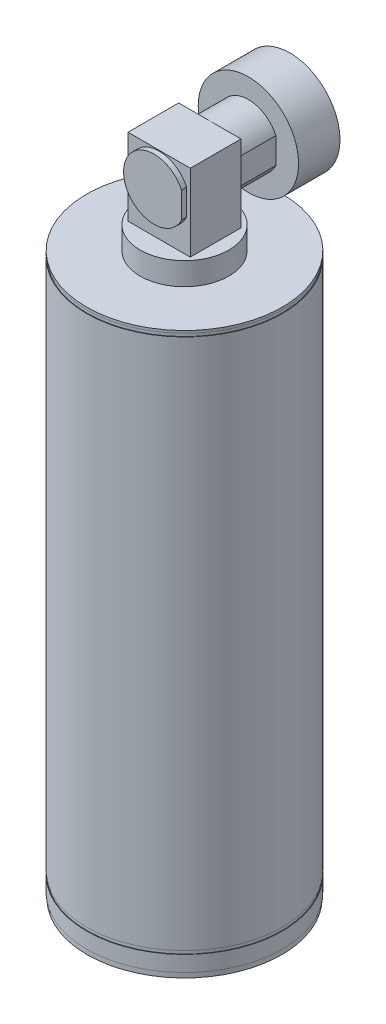
SolidWorks part; units mm, degrees
ref_plane "Front" through (0, 0, 0) normal (0, 0, 1) x (1, 0, 0)
ref_plane "Top" through (0, 0, 0) normal (0, 1, 0) x (1, 0, 0)
ref_plane "Right" through (0, 0, 0) normal (1, 0, 0) x (0, 0, -1)
sketch "Sketch2" plane through (0, -8703.7669, -206984.5906) normal (1, 0, 0) x (0, 0, -1)
  line L0 (-206984.5906, 9615.7669) -> (-206984.5906, 8710.7669)
  line L1 (-206838.5906, 8531.8824) -> (-206838.5906, 9181.9014)
  line L2 (-206850.8906, 8737.0763) -> (-206850.8906, 9470.4575)
  line L3 (-207118.2906, 9470.4575) -> (-207118.2906, 8737.0763)
  line L4 (-206984.5906, 8703.7669) -> (-206984.5906, 8496.5272)
  line L6 (-207008.7651, 8687.6953) -> (-207008.7651, 8625.8262)
  line L7 (-206959.4161, 8625.7814) -> (-206959.4161, 8687.6938)
  line L8 (-206955.5906, 8625.4453) -> (-206955.5906, 8687.3541)
  line L9 (-207013.5906, 8624.982) -> (-207013.5906, 8686.8426)
  line L10 (-207023.7901, 8632.7669) -> (-207023.7901, 8622.7669)
  line L11 (-206935.5906, 8639.3205) -> (-206935.5906, 8566.7669)
  line L12 (-206895.5906, 8550.8985) -> (-206895.5906, 8639.3205)
  line L13 (-206890.5906, 8637.2074) -> (-206890.5906, 8573.5089)
  line L14 (-206890.5906, 8631.7133) -> (-206890.5906, 8593.9991)
  line L15 (-206943.5906, 8571.7669) -> (-206943.5906, 8663.7669)
  line L16 (-206943.0906, 8664.2669) -> (-206943.0906, 8571.2669)
  line L17 (-206936.0906, 8571.2669) -> (-206936.0906, 8664.2669)
  line L18 (-206948.5906, 8596.3362) -> (-206948.5906, 8639.1977)
  line L19 (-207016.0901, 8635.2669) -> (-207016.0901, 8600.2669)
  line L20 (-206999.0901, 8635.2669) -> (-206999.0901, 8600.2669)
  line L21 (-207017.7901, 8583.7669) -> (-207017.7901, 8651.7669)
  line L22 (-207016.5901, 8583.7669) -> (-207016.5901, 8651.7669)
  line L23 (-207013.5906, 8624.982) -> (-207013.5905, 8624.9836)
  line L24 (-207013.5905, 8624.9836) -> (-207013.5904, 8624.9852)
  line L25 (-207013.5904, 8624.9852) -> (-207013.5903, 8624.9868)
  line L26 (-207013.5903, 8624.9868) -> (-207013.5901, 8624.9884)
  line L27 (-207013.5901, 8624.9884) -> (-207013.59, 8624.99)
  line L28 (-207013.59, 8624.99) -> (-207013.5899, 8624.9916)
  line L29 (-207013.5899, 8624.9916) -> (-207013.5897, 8624.9932)
  line L30 (-207013.5897, 8624.9932) -> (-207013.5896, 8624.9947)
  line L31 (-207013.5896, 8624.9947) -> (-207013.5894, 8624.9963)
  line L32 (-207013.5894, 8624.9963) -> (-207013.5893, 8624.9978)
  line L33 (-207013.5893, 8624.9978) -> (-207013.5891, 8624.9993)
  line L34 (-207013.5891, 8624.9993) -> (-207013.5889, 8625.0008)
  line L35 (-207013.5889, 8625.0008) -> (-207013.5887, 8625.0024)
  line L36 (-207013.5887, 8625.0024) -> (-207013.5885, 8625.0038)
  line L37 (-207013.5885, 8625.0038) -> (-207013.5883, 8625.0058)
  line L38 (-207013.5883, 8625.0058) -> (-207013.588, 8625.0078)
  line L39 (-207013.588, 8625.0078) -> (-207013.5876, 8625.0097)
  line L40 (-207013.5876, 8625.0097) -> (-207013.5873, 8625.0117)
  line L41 (-207013.5873, 8625.0117) -> (-207013.5869, 8625.0136)
  line L42 (-207013.5869, 8625.0136) -> (-207013.5865, 8625.0156)
  line L43 (-207013.5865, 8625.0156) -> (-207013.5861, 8625.0175)
  line L44 (-207013.5861, 8625.0175) -> (-207013.5857, 8625.0194)
  line L45 (-207013.5857, 8625.0194) -> (-207013.5852, 8625.0213)
  line L46 (-207013.5852, 8625.0213) -> (-207013.5841, 8625.0252)
  line L47 (-207013.5841, 8625.0252) -> (-207013.5832, 8625.0282)
  line L48 (-207013.5832, 8625.0282) -> (-207013.5823, 8625.0311)
  line L49 (-207013.5823, 8625.0311) -> (-207013.5813, 8625.0339)
  line L50 (-207013.5813, 8625.0339) -> (-207013.5803, 8625.0368)
  line L51 (-207013.5803, 8625.0368) -> (-207013.5792, 8625.0396)
  line L52 (-207013.5792, 8625.0396) -> (-207013.578, 8625.0425)
  line L53 (-207013.578, 8625.0425) -> (-207013.5768, 8625.0453)
  line L54 (-207013.5768, 8625.0453) -> (-207013.5756, 8625.048)
  line L55 (-207013.5756, 8625.048) -> (-207013.5743, 8625.0508)
  line L56 (-207013.5743, 8625.0508) -> (-207013.5727, 8625.0538)
  line L57 (-207013.5727, 8625.0538) -> (-207013.5712, 8625.0568)
  line L58 (-207013.5712, 8625.0568) -> (-207013.5696, 8625.0598)
  line L59 (-207013.5696, 8625.0598) -> (-207013.5679, 8625.0627)
  line L60 (-207013.5679, 8625.0627) -> (-207013.5662, 8625.0656)
  line L61 (-207013.5662, 8625.0656) -> (-207013.5645, 8625.0685)
  line L62 (-207013.5645, 8625.0685) -> (-207013.5627, 8625.0714)
  line L63 (-207013.5627, 8625.0714) -> (-207013.5609, 8625.0742)
  line L64 (-207013.5609, 8625.0742) -> (-207013.559, 8625.0771)
  line L65 (-207013.559, 8625.0771) -> (-207013.5571, 8625.0798)
  line L66 (-207013.5571, 8625.0798) -> (-207013.5549, 8625.0829)
  line L67 (-207013.5549, 8625.0829) -> (-207013.5527, 8625.0859)
  line L68 (-207013.5527, 8625.0859) -> (-207013.5504, 8625.089)
  line L69 (-207013.5504, 8625.089) -> (-207013.5481, 8625.0919)
  line L70 (-207013.5481, 8625.0919) -> (-207013.5458, 8625.0949)
  line L71 (-207013.5458, 8625.0949) -> (-207013.5434, 8625.0978)
  line L72 (-207013.5434, 8625.0978) -> (-207013.541, 8625.1007)
  line L73 (-207013.541, 8625.1007) -> (-207013.5386, 8625.1036)
  line L74 (-207013.5386, 8625.1036) -> (-207013.5361, 8625.1064)
  line L75 (-207013.5361, 8625.1064) -> (-207013.5336, 8625.1092)
  line L76 (-207013.5336, 8625.1092) -> (-207013.5308, 8625.1123)
  line L77 (-207013.5308, 8625.1123) -> (-207013.5279, 8625.1153)
  line L78 (-207013.5279, 8625.1153) -> (-207013.525, 8625.1183)
  line L79 (-207013.525, 8625.1183) -> (-207013.5221, 8625.1213)
  line L80 (-207013.5221, 8625.1213) -> (-207013.5192, 8625.1242)
  line L81 (-207013.5192, 8625.1242) -> (-207013.5162, 8625.1272)
  line L82 (-207013.5162, 8625.1272) -> (-207013.5132, 8625.13)
  line L83 (-207013.5132, 8625.13) -> (-207013.5102, 8625.1329)
  line L84 (-207013.5102, 8625.1329) -> (-207013.5071, 8625.1357)
  line L85 (-207013.5071, 8625.1357) -> (-207013.504, 8625.1385)
  line L86 (-207013.504, 8625.1385) -> (-207013.495, 8625.1464)
  line L87 (-207013.495, 8625.1464) -> (-207013.4859, 8625.154)
  line L88 (-207013.4859, 8625.154) -> (-207013.4766, 8625.1614)
  line L89 (-207013.4766, 8625.1614) -> (-207013.4671, 8625.1686)
  line L90 (-207013.4671, 8625.1686) -> (-207013.4575, 8625.1757)
  line L91 (-207013.4575, 8625.1757) -> (-207013.4477, 8625.1825)
  line L92 (-207013.4477, 8625.1825) -> (-207013.4379, 8625.1892)
  line L93 (-207013.4379, 8625.1892) -> (-207013.4279, 8625.1958)
  line L94 (-207013.4279, 8625.1958) -> (-207013.4179, 8625.2022)
  line L95 (-207013.4179, 8625.2022) -> (-207013.4077, 8625.2084)
  line L96 (-207013.4077, 8625.2084) -> (-207013.3951, 8625.216)
  line L97 (-207013.3951, 8625.216) -> (-207013.3824, 8625.2233)
  line L98 (-207013.3824, 8625.2233) -> (-207013.3696, 8625.2305)
  line L99 (-207013.3696, 8625.2305) -> (-207013.3567, 8625.2374)
  line L100 (-207013.3567, 8625.2374) -> (-207013.3437, 8625.2443)
  line L101 (-207013.3437, 8625.2443) -> (-207013.3306, 8625.2509)
  line L102 (-207013.3306, 8625.2509) -> (-207013.3175, 8625.2575)
  line L103 (-207013.3175, 8625.2575) -> (-207013.3043, 8625.2639)
  line L104 (-207013.3043, 8625.2639) -> (-207013.291, 8625.2701)
  line L105 (-207013.291, 8625.2701) -> (-207013.2777, 8625.2762)
  line L106 (-207013.2777, 8625.2762) -> (-207013.2616, 8625.2834)
  line L107 (-207013.2616, 8625.2834) -> (-207013.2456, 8625.2905)
  line L108 (-207013.2456, 8625.2905) -> (-207013.2294, 8625.2973)
  line L109 (-207013.2294, 8625.2973) -> (-207013.2132, 8625.3041)
  line L110 (-207013.2132, 8625.3041) -> (-207013.1969, 8625.3106)
  line L111 (-207013.1969, 8625.3106) -> (-207013.1806, 8625.3171)
  line L112 (-207013.1806, 8625.3171) -> (-207013.1642, 8625.3234)
  line L113 (-207013.1642, 8625.3234) -> (-207013.1478, 8625.3296)
  line L114 (-207013.1478, 8625.3296) -> (-207013.1313, 8625.3357)
  line L115 (-207013.1313, 8625.3357) -> (-207013.1148, 8625.3417)
  line L116 (-207013.1148, 8625.3417) -> (-207013.0955, 8625.3485)
  line L117 (-207013.0955, 8625.3485) -> (-207013.0762, 8625.3552)
  line L118 (-207013.0762, 8625.3552) -> (-207013.0569, 8625.3618)
  line L119 (-207013.0569, 8625.3618) -> (-207013.0375, 8625.3682)
  line L120 (-207013.0375, 8625.3682) -> (-207013.018, 8625.3745)
  line L121 (-207013.018, 8625.3745) -> (-207012.9985, 8625.3807)
  line L122 (-207012.9985, 8625.3807) -> (-207012.979, 8625.3868)
  line L123 (-207012.979, 8625.3868) -> (-207012.9595, 8625.3928)
  line L124 (-207012.9595, 8625.3928) -> (-207012.9399, 8625.3987)
  line L125 (-207012.9399, 8625.3987) -> (-207012.9203, 8625.4045)
  line L126 (-207012.9203, 8625.4045) -> (-207012.8979, 8625.4109)
  line L127 (-207012.8979, 8625.4109) -> (-207012.8755, 8625.4173)
  line L128 (-207012.8755, 8625.4173) -> (-207012.8531, 8625.4235)
  line L129 (-207012.8531, 8625.4235) -> (-207012.8306, 8625.4296)
  line L130 (-207012.8306, 8625.4296) -> (-207012.8081, 8625.4357)
  line L131 (-207012.8081, 8625.4357) -> (-207012.7855, 8625.4416)
  line L132 (-207012.7855, 8625.4416) -> (-207012.763, 8625.4474)
  line L133 (-207012.763, 8625.4474) -> (-207012.7404, 8625.4531)
  line L134 (-207012.7404, 8625.4531) -> (-207012.7178, 8625.4587)
  line L135 (-207012.7178, 8625.4587) -> (-207012.6952, 8625.4643)
  line L136 (-207012.6952, 8625.4643) -> (-207012.6698, 8625.4704)
  line L137 (-207012.6698, 8625.4704) -> (-207012.6444, 8625.4764)
  line L138 (-207012.6444, 8625.4764) -> (-207012.619, 8625.4822)
  line L139 (-207012.619, 8625.4822) -> (-207012.5936, 8625.488)
  line L140 (-207012.5936, 8625.488) -> (-207012.5682, 8625.4937)
  line L141 (-207012.5682, 8625.4937) -> (-207012.5427, 8625.4993)
  line L142 (-207012.5427, 8625.4993) -> (-207012.5172, 8625.5048)
  line L143 (-207012.5172, 8625.5048) -> (-207012.4917, 8625.5102)
  line L144 (-207012.4917, 8625.5102) -> (-207012.4662, 8625.5156)
  line L145 (-207012.4662, 8625.5156) -> (-207012.4407, 8625.5208)
  line L146 (-207012.4407, 8625.5208) -> (-207012.4125, 8625.5265)
  line L147 (-207012.4125, 8625.5265) -> (-207012.3843, 8625.5321)
  line L148 (-207012.3843, 8625.5321) -> (-207012.356, 8625.5376)
  line L149 (-207012.356, 8625.5376) -> (-207012.3278, 8625.543)
  line L150 (-207012.3278, 8625.543) -> (-207012.2995, 8625.5484)
  line L151 (-207012.2995, 8625.5484) -> (-207012.2712, 8625.5536)
  line L152 (-207012.2712, 8625.5536) -> (-207012.243, 8625.5588)
  line L153 (-207012.243, 8625.5588) -> (-207012.2147, 8625.5638)
  line L154 (-207012.2147, 8625.5638) -> (-207012.1863, 8625.5688)
  line L155 (-207012.1863, 8625.5688) -> (-207012.158, 8625.5738)
  line L156 (-207012.158, 8625.5738) -> (-207012.1271, 8625.579)
  line L157 (-207012.1271, 8625.579) -> (-207012.0962, 8625.5842)
  line L158 (-207012.0962, 8625.5842) -> (-207012.0653, 8625.5893)
  line L159 (-207012.0653, 8625.5893) -> (-207012.0343, 8625.5943)
  line L160 (-207012.0343, 8625.5943) -> (-207012.0034, 8625.5993)
  line L161 (-207012.0034, 8625.5993) -> (-207011.9724, 8625.6041)
  line L162 (-207011.9724, 8625.6041) -> (-207011.9414, 8625.6089)
  line L163 (-207011.9414, 8625.6089) -> (-207011.9105, 8625.6136)
  line L164 (-207011.9105, 8625.6136) -> (-207011.8795, 8625.6182)
  line L165 (-207011.8795, 8625.6182) -> (-207011.8484, 8625.6228)
  line L166 (-207011.8484, 8625.6228) -> (-207011.815, 8625.6276)
  line L167 (-207011.815, 8625.6276) -> (-207011.7816, 8625.6324)
  line L168 (-207011.7816, 8625.6324) -> (-207011.7482, 8625.637)
  line L169 (-207011.7482, 8625.637) -> (-207011.7148, 8625.6416)
  line L170 (-207011.7148, 8625.6416) -> (-207011.6813, 8625.6461)
  line L171 (-207011.6813, 8625.6461) -> (-207011.6479, 8625.6505)
  line L172 (-207011.6479, 8625.6505) -> (-207011.6144, 8625.6549)
  line L173 (-207011.6144, 8625.6549) -> (-207011.5809, 8625.6592)
  line L174 (-207011.5809, 8625.6592) -> (-207011.5474, 8625.6634)
  line L175 (-207011.5474, 8625.6634) -> (-207011.5139, 8625.6675)
  line L176 (-207011.5139, 8625.6675) -> (-207011.4785, 8625.6718)
  line L177 (-207011.4785, 8625.6718) -> (-207011.443, 8625.6761)
  line L178 (-207011.443, 8625.6761) -> (-207011.4075, 8625.6802)
  line L179 (-207011.4075, 8625.6802) -> (-207011.3721, 8625.6843)
  line L180 (-207011.3721, 8625.6843) -> (-207011.3366, 8625.6883)
  line L181 (-207011.3366, 8625.6883) -> (-207011.3011, 8625.6922)
  line L182 (-207011.3011, 8625.6922) -> (-207011.2656, 8625.6961)
  line L183 (-207011.2656, 8625.6961) -> (-207011.2301, 8625.6999)
  line L184 (-207011.2301, 8625.6999) -> (-207011.1945, 8625.7036)
  line L185 (-207011.1945, 8625.7036) -> (-207011.159, 8625.7073)
  line L186 (-207011.159, 8625.7073) -> (-207011.1221, 8625.711)
  line L187 (-207011.1221, 8625.711) -> (-207011.0851, 8625.7147)
  line L188 (-207011.0851, 8625.7147) -> (-207011.0481, 8625.7182)
  line L189 (-207011.0481, 8625.7182) -> (-207011.0111, 8625.7218)
  line L190 (-207011.0111, 8625.7218) -> (-207010.9741, 8625.7252)
  line L191 (-207010.9741, 8625.7252) -> (-207010.9371, 8625.7286)
  line L192 (-207010.9371, 8625.7286) -> (-207010.9001, 8625.7319)
  line L193 (-207010.9001, 8625.7319) -> (-207010.8631, 8625.7351)
  line L194 (-207010.8631, 8625.7351) -> (-207010.8261, 8625.7382)
  line L195 (-207010.8261, 8625.7382) -> (-207010.7891, 8625.7413)
  line L196 (-207010.7891, 8625.7413) -> (-207010.7511, 8625.7444)
  line L197 (-207010.7511, 8625.7444) -> (-207010.7132, 8625.7474)
  line L198 (-207010.7132, 8625.7474) -> (-207010.6752, 8625.7504)
  line L199 (-207010.6752, 8625.7504) -> (-207010.6372, 8625.7532)
  line L200 (-207010.6372, 8625.7532) -> (-207010.5992, 8625.756)
  line L201 (-207010.5992, 8625.756) -> (-207010.5613, 8625.7587)
  line L202 (-207010.5613, 8625.7587) -> (-207010.5233, 8625.7614)
  line L203 (-207010.5233, 8625.7614) -> (-207010.4853, 8625.764)
  line L204 (-207010.4853, 8625.764) -> (-207010.4473, 8625.7665)
  line L205 (-207010.4473, 8625.7665) -> (-207010.4093, 8625.7689)
  line L206 (-207010.4093, 8625.7689) -> (-207010.3707, 8625.7713)
  line L207 (-207010.3707, 8625.7713) -> (-207010.3321, 8625.7736)
  line L208 (-207010.3321, 8625.7736) -> (-207010.2934, 8625.7758)
  line L209 (-207010.2934, 8625.7758) -> (-207010.2548, 8625.778)
  line L210 (-207010.2548, 8625.778) -> (-207010.2162, 8625.7801)
  line L211 (-207010.2162, 8625.7801) -> (-207010.1776, 8625.7822)
  line L212 (-207010.1776, 8625.7822) -> (-207010.1389, 8625.7841)
  line L213 (-207010.1389, 8625.7841) -> (-207010.1003, 8625.786)
  line L214 (-207010.1003, 8625.786) -> (-207010.0616, 8625.7879)
  line L215 (-207010.0616, 8625.7879) -> (-207010.023, 8625.7897)
  line L216 (-207010.023, 8625.7897) -> (-207009.9832, 8625.7914)
  line L217 (-207009.9832, 8625.7914) -> (-207009.9434, 8625.7931)
  line L218 (-207009.9434, 8625.7931) -> (-207009.9036, 8625.7948)
  line L219 (-207009.9036, 8625.7948) -> (-207009.8638, 8625.7964)
  line L220 (-207009.8638, 8625.7964) -> (-207009.824, 8625.798)
  line L221 (-207009.824, 8625.798) -> (-207009.7842, 8625.7995)
  line L222 (-207009.7842, 8625.7995) -> (-207009.7444, 8625.8009)
  line L223 (-207009.7444, 8625.8009) -> (-207009.7046, 8625.8023)
  line L224 (-207009.7046, 8625.8023) -> (-207009.6648, 8625.8037)
  line L225 (-207009.6648, 8625.8037) -> (-207009.625, 8625.805)
  line L226 (-207009.625, 8625.805) -> (-207009.5833, 8625.8063)
  line L227 (-207009.5833, 8625.8063) -> (-207009.5416, 8625.8076)
  line L228 (-207009.5416, 8625.8076) -> (-207009.4999, 8625.8088)
  line L229 (-207009.4999, 8625.8088) -> (-207009.4582, 8625.81)
  line L230 (-207009.4582, 8625.81) -> (-207009.4165, 8625.8112)
  line L231 (-207009.4165, 8625.8112) -> (-207009.3749, 8625.8123)
  line L232 (-207009.3749, 8625.8123) -> (-207009.3332, 8625.8134)
  line L233 (-207009.3332, 8625.8134) -> (-207009.2915, 8625.8145)
  line L234 (-207009.2915, 8625.8145) -> (-207009.2498, 8625.8156)
  line L235 (-207009.2498, 8625.8156) -> (-207009.2081, 8625.8166)
  line L236 (-207009.2081, 8625.8166) -> (-207009.1638, 8625.8176)
  line L237 (-207009.1638, 8625.8176) -> (-207009.1195, 8625.8187)
  line L238 (-207009.1195, 8625.8187) -> (-207009.0752, 8625.8197)
  line L239 (-207009.0752, 8625.8197) -> (-207009.0309, 8625.8207)
  line L240 (-207009.0309, 8625.8207) -> (-207008.9866, 8625.8216)
  line L241 (-207008.9866, 8625.8216) -> (-207008.9423, 8625.8226)
  line L242 (-207008.9423, 8625.8226) -> (-207008.898, 8625.8235)
  line L243 (-207008.898, 8625.8235) -> (-207008.8537, 8625.8244)
  line L244 (-207008.8537, 8625.8244) -> (-207008.8094, 8625.8253)
  line L245 (-207008.8094, 8625.8253) -> (-207008.7651, 8625.8262)
  line L246 (-206984.5906, 8625.9279) -> (-207008.7651, 8625.8262)
  line L247 (-206984.588, 8626.2792) -> (-206984.5906, 8625.9279)
  line L248 (-206984.588, 8626.2792) -> (-206984.5878, 8626.3055)
  line L250 (-207023.7901, 8622.7669) -> (-207017.7901, 8622.7669)
  line L251 (-207017.7901, 8612.7669) -> (-207023.7901, 8612.7669)
  line L252 (-206927.1136, 8544.8619) -> (-206927.4011, 8541.5419)
  line L253 (-206927.1136, 8544.8619) -> (-206927.4252, 8544.8627)
  line L254 (-206927.4252, 8544.8627) -> (-206927.7344, 8544.8433)
  line L255 (-206927.7344, 8544.8433) -> (-206928.0385, 8544.8039)
  line L256 (-206928.0385, 8544.8039) -> (-206928.3354, 8544.7447)
  line L257 (-206928.3354, 8544.7447) -> (-206928.6225, 8544.6663)
  line L258 (-206928.6225, 8544.6663) -> (-206928.8976, 8544.5692)
  line L259 (-206928.8976, 8544.5692) -> (-206929.1584, 8544.4543)
  line L260 (-206929.1584, 8544.4543) -> (-206929.403, 8544.3225)
  line L261 (-206929.403, 8544.3225) -> (-206929.6294, 8544.1747)
  line L262 (-206929.6294, 8544.1747) -> (-206929.8357, 8544.0122)
  line L263 (-206929.8357, 8544.0122) -> (-206930.0204, 8543.8363)
  line L264 (-206930.0204, 8543.8363) -> (-206930.1819, 8543.6484)
  line L265 (-206930.1819, 8543.6484) -> (-206930.3189, 8543.45)
  line L266 (-206930.3189, 8543.45) -> (-206930.4305, 8543.2426)
  line L267 (-206930.4305, 8543.2426) -> (-206930.5156, 8543.0279)
  line L268 (-206930.5156, 8543.0279) -> (-206930.5737, 8542.8076)
  line L269 (-206930.5737, 8542.8076) -> (-206930.6041, 8542.5835)
  line L270 (-206927.0906, 8550.8985) -> (-206927.4136, 8550.8922)
  line L271 (-206927.4136, 8550.8922) -> (-206927.7337, 8550.8733)
  line L272 (-206927.7337, 8550.8733) -> (-206928.0485, 8550.8421)
  line L273 (-206928.0485, 8550.8421) -> (-206928.355, 8550.7986)
  line L274 (-206928.355, 8550.7986) -> (-206928.6507, 8550.7435)
  line L275 (-206928.6507, 8550.7435) -> (-206928.9331, 8550.677)
  line L276 (-206928.9331, 8550.677) -> (-206929.1999, 8550.5998)
  line L277 (-206929.1999, 8550.5998) -> (-206929.4486, 8550.5125)
  line L278 (-206929.4486, 8550.5125) -> (-206929.6772, 8550.4159)
  line L279 (-206929.6772, 8550.4159) -> (-206929.8837, 8550.3108)
  line L280 (-206929.8837, 8550.3108) -> (-206930.0664, 8550.198)
  line L281 (-206930.0664, 8550.198) -> (-206930.2237, 8550.0787)
  line L282 (-206930.2237, 8550.0787) -> (-206930.3543, 8549.9537)
  line L283 (-206930.3543, 8549.9537) -> (-206930.457, 8549.8242)
  line L284 (-206930.457, 8549.8242) -> (-206930.531, 8549.6912)
  line L285 (-206930.531, 8549.6912) -> (-206930.5757, 8549.5558)
  line L286 (-206930.5757, 8549.5558) -> (-206930.5906, 8549.4194)
  line L287 (-206927.0906, 8545.3934) -> (-206927.4136, 8545.383)
  line L288 (-206927.4136, 8545.383) -> (-206927.7337, 8545.3519)
  line L289 (-206927.7337, 8545.3519) -> (-206928.0485, 8545.3002)
  line L290 (-206928.0485, 8545.3002) -> (-206928.355, 8545.2285)
  line L291 (-206928.355, 8545.2285) -> (-206928.6507, 8545.1374)
  line L292 (-206928.6507, 8545.1374) -> (-206928.9331, 8545.0276)
  line L293 (-206928.9331, 8545.0276) -> (-206929.1999, 8544.9001)
  line L294 (-206929.1999, 8544.9001) -> (-206929.4486, 8544.756)
  line L295 (-206929.4486, 8544.756) -> (-206929.6772, 8544.5964)
  line L296 (-206929.6772, 8544.5964) -> (-206929.8837, 8544.4229)
  line L297 (-206929.8837, 8544.4229) -> (-206930.0664, 8544.2367)
  line L298 (-206930.0664, 8544.2367) -> (-206930.2237, 8544.0396)
  line L299 (-206930.2237, 8544.0396) -> (-206930.3543, 8543.8332)
  line L300 (-206930.3543, 8543.8332) -> (-206930.457, 8543.6193)
  line L301 (-206930.457, 8543.6193) -> (-206930.531, 8543.3997)
  line L302 (-206930.531, 8543.3997) -> (-206930.5757, 8543.1763)
  line L303 (-206930.5757, 8543.1763) -> (-206930.5906, 8542.9509)
  line L304 (-206930.6041, 8542.5835) -> (-206930.5906, 8542.9509)
  line L305 (-206927.0906, 8550.8985) -> (-206927.0906, 8545.3934)
  line L306 (-206927.0906, 8545.3934) -> (-206927.1136, 8544.8619)
  line L307 (-206927.0906, 8550.8985) -> (-206895.5906, 8550.8985)
  line L308 (-206930.5906, 8542.9509) -> (-206930.5906, 8549.4194)
  line L309 (-206930.5906, 8544.7674) -> (-206930.5906, 8560.7669)
  line L310 (-207016.0901, 8600.2669) -> (-207013.5906, 8600.2669)
  line L311 (-207016.5901, 8600.7669) -> (-207016.0901, 8600.2669)
  line L312 (-206955.5906, 8593.7669) -> (-206952.7906, 8593.7669)
  line L313 (-206943.0906, 8571.2669) -> (-206936.0906, 8571.2669)
  line L314 (-207016.9021, 8601.0789) -> (-206999.0901, 8601.0789)
  line L315 (-206984.5906, 8568.7669) -> (-206959.4161, 8569.6461)
  line L316 (-207008.7651, 8569.6111) -> (-206984.5906, 8568.7669)
  line L317 (-206943.5906, 8583.3362) -> (-206943.5906, 8585.24)
  line L318 (-206943.5906, 8596.3362) -> (-206944.7906, 8596.3362)
  line L319 (-206944.7906, 8583.3362) -> (-206943.5906, 8583.3362)
  line L320 (-206944.7906, 8583.3362) -> (-206944.7906, 8596.3362)
  line L321 (-206952.7906, 8583.3362) -> (-206944.7906, 8583.3362)
  line L322 (-206944.7906, 8596.3362) -> (-206952.7906, 8596.3362)
  line L323 (-206952.7906, 8596.3362) -> (-206952.7906, 8583.3362)
  line L324 (-206944.7906, 8596.3362) -> (-206944.7906, 8583.3362)
  line L325 (-207017.7901, 8583.7669) -> (-207016.5901, 8583.7669)
  line L326 (-207023.7901, 8602.7669) -> (-207017.7901, 8602.7669)
  line L327 (-206955.5906, 8571.643) -> (-206955.5906, 8625.4453)
  line L328 (-207013.5906, 8574.6081) -> (-207013.5906, 8624.982)
  line L329 (-206959.4161, 8569.6461) -> (-206959.4161, 8625.7814)
  line L330 (-207008.7651, 8625.8262) -> (-207008.7651, 8569.6111)
  line L331 (-206984.5906, 8568.7669) -> (-206984.5906, 8625.9279)
  line L332 (-207023.7901, 8612.7669) -> (-207023.7901, 8602.7669)
  line L333 (-206935.5906, 8668.7669) -> (-206935.5906, 8639.3205)
  line L334 (-206935.5906, 8639.3205) -> (-206895.5906, 8639.3205)
  line L335 (-206895.5906, 8668.7669) -> (-206895.5906, 8639.3205)
  line L336 (-206890.5906, 8663.7669) -> (-206890.5906, 8637.2074)
  line L337 (-206890.5906, 8637.2074) -> (-206890.6097, 8637.3915)
  line L338 (-206890.6097, 8637.3915) -> (-206890.6666, 8637.5743)
  line L339 (-206890.6666, 8637.5743) -> (-206890.761, 8637.7543)
  line L340 (-206890.761, 8637.7543) -> (-206890.8922, 8637.9301)
  line L341 (-206890.8922, 8637.9301) -> (-206891.0591, 8638.1004)
  line L342 (-206891.0591, 8638.1004) -> (-206891.2605, 8638.2639)
  line L343 (-206891.2605, 8638.2639) -> (-206891.4949, 8638.4194)
  line L344 (-206891.4949, 8638.4194) -> (-206891.7604, 8638.5656)
  line L345 (-206891.7604, 8638.5656) -> (-206892.0551, 8638.7016)
  line L346 (-206892.0551, 8638.7016) -> (-206892.3767, 8638.8261)
  line L347 (-206892.3767, 8638.8261) -> (-206892.7227, 8638.9383)
  line L348 (-206892.7227, 8638.9383) -> (-206893.0906, 8639.0374)
  line L349 (-206893.0906, 8639.0374) -> (-206893.4775, 8639.1225)
  line L350 (-206893.4775, 8639.1225) -> (-206893.8805, 8639.193)
  line L351 (-206893.8805, 8639.193) -> (-206894.2965, 8639.2485)
  line L352 (-206894.2965, 8639.2485) -> (-206894.7224, 8639.2884)
  line L353 (-206894.7224, 8639.2884) -> (-206895.1548, 8639.3124)
  line L354 (-206895.1548, 8639.3124) -> (-206895.5906, 8639.3205)
  line L355 (-206890.5906, 8631.7133) -> (-206890.5906, 8650.7669)
  line L356 (-206895.5906, 8668.7669) -> (-206935.5906, 8668.7669)
  line L357 (-207013.5906, 8635.2669) -> (-207016.0901, 8635.2669)
  line L358 (-206952.7906, 8641.7669) -> (-206955.5906, 8641.7669)
  line L359 (-206936.0906, 8664.2669) -> (-206943.0906, 8664.2669)
  line L360 (-207016.0901, 8635.2669) -> (-207016.5901, 8634.7669)
  line L361 (-207016.9021, 8634.4549) -> (-206999.0901, 8634.4549)
  line L362 (-207118.2906, 8737.0763) -> (-206850.8906, 8737.0763)
  line L363 (-206850.8906, 8710.7669) -> (-207118.2906, 8710.7669)
  line L364 (-206850.8906, 8732.4575) -> (-207118.2906, 8732.4575)
  line L365 (-206850.8906, 8710.7669) -> (-206850.8906, 8732.4575)
  line L366 (-207118.2906, 8732.4575) -> (-207118.2906, 8710.7669)
  line L367 (-206850.8906, 8737.0763) -> (-207118.2906, 8737.0763)
  line L368 (-206850.8906, 8732.4575) -> (-207118.2906, 8732.4575)
  line L369 (-206850.8906, 8703.7669) -> (-206850.8906, 8710.7669)
  line L370 (-207118.2906, 8710.7669) -> (-206850.8906, 8710.7669)
  line L371 (-207118.2906, 8703.7669) -> (-206850.8906, 8703.7669)
  line L372 (-207118.2906, 8710.7669) -> (-207118.2906, 8703.7669)
  line L373 (-206964.5906, 8690.5669) -> (-206964.5906, 8703.7669)
  line L374 (-207004.5906, 8703.7669) -> (-207004.5906, 8690.5669)
  line L376 (-207012.5281, 8690.2669) -> (-207008.8269, 8690.2669)
  line L377 (-207008.8269, 8690.2669) -> (-206990.5025, 8690.2669)
  line L378 (-207008.7651, 8687.6953) -> (-207009.2152, 8687.6891)
  line L379 (-207009.2152, 8687.6891) -> (-207009.6603, 8687.6761)
  line L380 (-207009.6603, 8687.6761) -> (-207010.0966, 8687.6562)
  line L381 (-207010.0966, 8687.6562) -> (-207010.5206, 8687.6297)
  line L382 (-207010.5206, 8687.6297) -> (-207010.9289, 8687.5968)
  line L383 (-207010.9289, 8687.5968) -> (-207011.3181, 8687.5577)
  line L384 (-207011.3181, 8687.5577) -> (-207011.6851, 8687.5128)
  line L385 (-207011.6851, 8687.5128) -> (-207012.0268, 8687.4624)
  line L386 (-207012.0268, 8687.4624) -> (-207012.3405, 8687.407)
  line L387 (-207012.3405, 8687.407) -> (-207012.6236, 8687.347)
  line L388 (-207012.6236, 8687.347) -> (-207012.8738, 8687.2828)
  line L389 (-207012.8738, 8687.2828) -> (-207013.0891, 8687.2151)
  line L390 (-207013.0891, 8687.2151) -> (-207013.2677, 8687.1443)
  line L391 (-207013.2677, 8687.1443) -> (-207013.4081, 8687.0711)
  line L392 (-207013.4081, 8687.0711) -> (-207013.5092, 8686.996)
  line L393 (-207013.5092, 8686.996) -> (-207013.5702, 8686.9196)
  line L394 (-207013.5702, 8686.9196) -> (-207013.5906, 8686.8426)
  line L395 (-206955.5906, 8687.3541) -> (-206955.5906, 8690.1853)
  line L396 (-206955.5906, 8687.3541) -> (-206955.8739, 8687.4127)
  line L397 (-206955.8739, 8687.4127) -> (-206956.1868, 8687.4668)
  line L398 (-206956.1868, 8687.4668) -> (-206956.5267, 8687.5159)
  line L399 (-206956.5267, 8687.5159) -> (-206956.891, 8687.5597)
  line L400 (-206956.891, 8687.5597) -> (-206957.2769, 8687.5978)
  line L401 (-206957.2769, 8687.5978) -> (-206957.6811, 8687.6299)
  line L402 (-206957.6811, 8687.6299) -> (-206958.1005, 8687.6557)
  line L403 (-206958.1005, 8687.6557) -> (-206958.5318, 8687.6751)
  line L404 (-206958.5318, 8687.6751) -> (-206958.9715, 8687.6878)
  line L405 (-206958.9715, 8687.6878) -> (-206959.4161, 8687.6938)
  line L406 (-207013.5906, 8686.8426) -> (-207013.5906, 8687.1853)
  line L407 (-206959.3539, 8690.2669) -> (-206955.6532, 8690.2669)
  line L408 (-206977.7023, 8690.2669) -> (-206959.3539, 8690.2669)
  line L410 (-206990.2062, 8688.0012) -> (-207008.7651, 8687.6953)
  line L412 (-206959.4161, 8687.6938) -> (-206978.0593, 8688.0051)
  line L415 (-206851.5906, 8702.5669) -> (-206864.5906, 8702.5669)
  line L416 (-206864.5906, 8703.7669) -> (-206864.5906, 8702.5669)
  line L417 (-206851.5906, 8702.5669) -> (-206851.5906, 8703.7669)
  line L418 (-206864.5906, 8694.5669) -> (-206851.5906, 8694.5669)
  line L419 (-206864.5906, 8702.5669) -> (-206851.5906, 8702.5669)
  line L420 (-206851.5906, 8694.5669) -> (-206851.5906, 8702.5669)
  line L421 (-206864.5906, 8702.5669) -> (-206864.5906, 8694.5669)
  line L422 (-206888.6416, 8702.5669) -> (-206901.6416, 8702.5669)
  line L423 (-206901.6416, 8703.7669) -> (-206901.6416, 8702.5669)
  line L424 (-206888.6416, 8702.5669) -> (-206888.6416, 8703.7669)
  line L425 (-206901.6416, 8694.5669) -> (-206888.6416, 8694.5669)
  line L426 (-206888.6416, 8694.5669) -> (-206888.6416, 8702.5669)
  line L427 (-206901.6416, 8702.5669) -> (-206901.6416, 8694.5669)
  line L428 (-206901.6416, 8702.5669) -> (-206888.6416, 8702.5669)
  line L429 (-206978.0906, 8702.5669) -> (-206991.0906, 8702.5669)
  line L430 (-206991.0906, 8703.7669) -> (-206991.0906, 8702.5669)
  line L431 (-206978.0906, 8702.5669) -> (-206978.0906, 8703.7669)
  line L432 (-206978.0906, 8694.5669) -> (-206978.0906, 8702.5669)
  line L433 (-206991.0906, 8702.5669) -> (-206991.0906, 8694.5669)
  line L434 (-206991.0906, 8702.5669) -> (-206978.0906, 8702.5669)
  line L435 (-206991.0906, 8694.5669) -> (-206978.0906, 8694.5669)
  line L436 (-207080.5396, 8703.7669) -> (-207080.5396, 8702.5669)
  line L437 (-207067.5396, 8702.5669) -> (-207067.5396, 8703.7669)
  line L438 (-207067.5396, 8702.5669) -> (-207080.5396, 8702.5669)
  line L439 (-207080.5396, 8694.5669) -> (-207067.5396, 8694.5669)
  line L440 (-207067.5396, 8694.5669) -> (-207067.5396, 8702.5669)
  line L441 (-207080.5396, 8702.5669) -> (-207080.5396, 8694.5669)
  line L442 (-207080.5396, 8702.5669) -> (-207067.5396, 8702.5669)
  line L443 (-207117.5906, 8703.7669) -> (-207117.5906, 8702.5669)
  line L444 (-207104.5906, 8702.5669) -> (-207104.5906, 8703.7669)
  line L445 (-207104.5906, 8702.5669) -> (-207117.5906, 8702.5669)
  line L446 (-207104.5906, 8694.5669) -> (-207104.5906, 8702.5669)
  line L447 (-207117.5906, 8702.5669) -> (-207117.5906, 8694.5669)
  line L448 (-207117.5906, 8702.5669) -> (-207104.5906, 8702.5669)
  line L449 (-207117.5906, 8694.5669) -> (-207104.5906, 8694.5669)
  line L450 (-206951.6599, 8696.7669) -> (-206951.6599, 8702.7669)
  line L451 (-206961.6599, 8702.7669) -> (-206961.6599, 8696.7669)
  line L452 (-206961.6599, 8702.7669) -> (-206951.6599, 8702.7669)
  line L453 (-206961.6599, 8696.7669) -> (-206951.6599, 8696.7669)
  line L454 (-206951.6599, 8702.7669) -> (-206961.6599, 8702.7669)
  line L455 (-206961.6599, 8703.7669) -> (-206961.6599, 8702.7669)
  line L456 (-206951.6599, 8702.7669) -> (-206951.6599, 8703.7669)
  line L457 (-207007.5213, 8696.7669) -> (-207007.5213, 8702.7669)
  line L458 (-207017.5213, 8702.7669) -> (-207017.5213, 8696.7669)
  line L459 (-207017.5213, 8702.7669) -> (-207007.5213, 8702.7669)
  line L460 (-207017.5213, 8696.7669) -> (-207007.5213, 8696.7669)
  line L461 (-207007.5213, 8702.7669) -> (-207017.5213, 8702.7669)
  line L462 (-207017.5213, 8703.7669) -> (-207017.5213, 8702.7669)
  line L463 (-207007.5213, 8702.7669) -> (-207007.5213, 8703.7669)
  line L464 (-206944.7906, 8639.1977) -> (-206944.7906, 8652.1977)
  line L465 (-206943.5906, 8650.2938) -> (-206943.5906, 8652.1977)
  line L466 (-206943.5906, 8652.1977) -> (-206944.7906, 8652.1977)
  line L467 (-206944.7906, 8639.1977) -> (-206943.5906, 8639.1977)
  line L468 (-206952.7906, 8652.1977) -> (-206952.7906, 8639.1977)
  line L469 (-206952.7906, 8639.1977) -> (-206944.7906, 8639.1977)
  line L470 (-206944.7906, 8652.1977) -> (-206952.7906, 8652.1977)
  line L471 (-206944.7906, 8652.1977) -> (-206944.7906, 8639.1977)
  line L472 (-207016.5901, 8651.7669) -> (-207017.7901, 8651.7669)
  line L473 (-207017.7901, 8632.7669) -> (-207023.7901, 8632.7669)
  line L474 (-206838.5906, 9187.1109) -> (-206838.5906, 9347.379)
  line L475 (-206838.5906, 9181.9014) -> (-206838.5906, 9187.1109)
  line L476 (-207043.5906, 9509.7669) -> (-207043.5906, 9478.2669)
  line L477 (-206925.5906, 9478.2669) -> (-206925.5906, 9509.7669)
  line L478 (-206844.8406, 9489.7669) -> (-206844.8406, 9439.7669)
  line L479 (-207118.2906, 9470.4575) -> (-206850.8906, 9470.4575)
  line L480 (-207118.2906, 9478.2669) -> (-206850.8906, 9478.2669)
  line L481 (-206850.8906, 9475.0763) -> (-207118.2906, 9475.0763)
  line L482 (-207118.2906, 9478.2669) -> (-207118.2906, 9475.0763)
  line L483 (-206850.8906, 9475.0763) -> (-206850.8906, 9478.2669)
  line L484 (-206850.8906, 9475.0763) -> (-207118.2906, 9475.0763)
  line L485 (-206850.8906, 9470.4575) -> (-207118.2906, 9470.4575)
  line L486 (-206838.5906, 9347.379) -> (-206838.5906, 9351.4415)
  line L487 (-206838.5906, 9351.4415) -> (-206838.5906, 9426.1669)
  line L488 (-206844.8406, 9439.7669) -> (-206843.8406, 9438.7669)
  line L489 (-206836.1741, 9437.5669) -> (-206836.1741, 9429.5669)
  line L490 (-206823.1741, 9429.5669) -> (-206836.1741, 9429.5669)
  line L491 (-206823.1741, 9437.5669) -> (-206836.1741, 9437.5669)
  line L492 (-206836.1741, 9438.7669) -> (-206834.7308, 9438.7669)
  line L493 (-206836.1741, 9438.7669) -> (-206836.1741, 9437.5669)
  line L494 (-206836.1741, 9437.5669) -> (-206823.1741, 9437.5669)
  line L495 (-206837.2181, 9433.7669) -> (-206836.1741, 9433.7669)
  line L496 (-206837.2181, 9438.7669) -> (-206836.5179, 9438.7669)
  line L497 (-206837.2181, 9438.7669) -> (-206837.2181, 9433.7669)
  line L498 (-206844.5906, 9438.7669) -> (-206837.2181, 9438.7669)
  line L499 (-206844.5906, 9433.7669) -> (-206837.2181, 9433.7669)
  line L500 (-206844.5906, 9438.7669) -> (-206844.5906, 9433.7669)
  line L501 (-206842.9509, 9433.7669) -> (-206842.9509, 9432.1669)
  line L502 (-206842.9509, 9432.1669) -> (-206836.1741, 9432.1669)
  line L503 (-206831.7009, 9426.1669) -> (-206831.7009, 9429.5669)
  line L504 (-206841.7009, 9432.1669) -> (-206841.7009, 9426.1669)
  line L505 (-206831.7009, 9426.1669) -> (-206841.7009, 9426.1669)
  line L506 (-206855.5906, 9487.7669) -> (-206848.5906, 9487.7669)
  line L507 (-206855.5906, 9501.7669) -> (-206855.5906, 9487.7669)
  line L508 (-206848.5906, 9487.7669) -> (-206848.5906, 9495.7669)
  line L509 (-206908.0906, 9599.2669) -> (-206949.5906, 9599.2669)
  line L510 (-206949.5906, 9546.2669) -> (-206908.0906, 9546.2669)
  line L511 (-207019.5906, 9509.7669) -> (-207019.5906, 9615.7669)
  line L512 (-206949.5906, 9509.7669) -> (-206949.5906, 9615.7669)
  line L513 (-206949.5906, 9615.7669) -> (-207019.5906, 9615.7669)
  line L514 (-206925.5906, 9509.7669) -> (-207043.5906, 9509.7669)
  line L515 (-207022.6356, 9509.7669) -> (-207022.6356, 9511.2669)
  line L516 (-207038.6356, 9511.2669) -> (-207038.6356, 9509.7669)
  line L517 (-207038.6356, 9511.2669) -> (-207022.6356, 9511.2669)
  line L518 (-207022.6356, 9511.2669) -> (-207038.6356, 9511.2669)
  line L519 (-207022.6356, 9521.2669) -> (-207038.6356, 9521.2669)
  line L520 (-207038.6356, 9521.2669) -> (-207038.6356, 9511.2669)
  line L521 (-207022.6356, 9511.2669) -> (-207022.6356, 9521.2669)
  line L522 (-206930.5457, 9521.2669) -> (-206946.5457, 9521.2669)
  line L523 (-206946.5457, 9521.2669) -> (-206946.5457, 9511.2669)
  line L524 (-206930.5457, 9511.2669) -> (-206930.5457, 9521.2669)
  line L525 (-206930.5457, 9511.2669) -> (-206946.5457, 9511.2669)
  line L526 (-206930.5457, 9509.7669) -> (-206930.5457, 9511.2669)
  line L527 (-206946.5457, 9511.2669) -> (-206946.5457, 9509.7669)
  line L528 (-206946.5457, 9511.2669) -> (-206930.5457, 9511.2669)
  line L529 (-207023.5906, 9614.7669) -> (-207023.5906, 9530.7669)
  line L530 (-207023.5906, 9530.7669) -> (-207019.5906, 9530.7669)
  line L531 (-207019.5906, 9614.7669) -> (-207023.5906, 9614.7669)
  line L532 (-207026.5906, 9533.7669) -> (-207026.5906, 9611.7669)
  line L533 (-207023.5906, 9614.7669) -> (-207026.5906, 9611.7669)
  line L534 (-207026.5906, 9533.7669) -> (-207023.5906, 9530.7669)
  line L535 (-206895.0906, 9507.7669) -> (-206889.2935, 9507.7669)
  line L536 (-206896.2906, 9508.9669) -> (-206896.2906, 9515.1947)
  line L537 (-206895.0906, 9513.5104) -> (-206895.0906, 9507.7669)
  line L538 (-206852.5906, 9501.3836) -> (-206852.5906, 9495.7669)
  line L539 (-206686.3968, 9496.7669) -> (-206849.5906, 9496.7669)
  line L540 (-206908.0906, 9529.408) -> (-206908.0906, 9528.2471)
  line L541 (-206908.0906, 9529.408) -> (-206908.0716, 9529.012)
  line L542 (-206908.0716, 9529.012) -> (-206908.0147, 9528.619)
  line L543 (-206908.0147, 9528.619) -> (-206907.9203, 9528.2321)
  line L544 (-206907.9203, 9528.2321) -> (-206907.7891, 9527.854)
  line L545 (-206907.7891, 9527.854) -> (-206907.6222, 9527.4878)
  line L546 (-206907.6222, 9527.4878) -> (-206907.4208, 9527.1362)
  line L547 (-206907.4208, 9527.1362) -> (-206907.1864, 9526.8019)
  line L548 (-206907.1864, 9526.8019) -> (-206906.9208, 9526.4875)
  line L549 (-206906.9208, 9526.4875) -> (-206906.6262, 9526.1952)
  line L550 (-206906.6262, 9526.1952) -> (-206906.3046, 9525.9275)
  line L551 (-206906.3046, 9525.9275) -> (-206905.9585, 9525.6862)
  line L552 (-206905.9585, 9525.6862) -> (-206905.5906, 9525.4732)
  line L553 (-206905.5906, 9525.4732) -> (-206905.2037, 9525.2902)
  line L554 (-206905.2037, 9525.2902) -> (-206904.8007, 9525.1385)
  line L555 (-206904.8007, 9525.1385) -> (-206904.3847, 9525.0193)
  line L556 (-206904.3847, 9525.0193) -> (-206903.9589, 9524.9335)
  line L557 (-206903.9589, 9524.9335) -> (-206903.5264, 9524.8817)
  line L558 (-206903.5264, 9524.8817) -> (-206903.0906, 9524.8645)
  line L559 (-206903.0906, 9540.7669) -> (-206908.0906, 9540.7669)
  line L560 (-206851.7553, 9501.7669) -> (-206858.5011, 9501.7669)
  line L561 (-206900.8639, 9540.7669) -> (-206903.0906, 9540.7669)
  line L562 (-206846.9662, 9496.8669) -> (-206849.5906, 9496.8669)
  line L563 (-206840.136, 9503.7669) -> (-206840.1884, 9503.6801)
  line L564 (-206840.1884, 9503.6801) -> (-206840.2408, 9503.5932)
  line L565 (-206840.2408, 9503.5932) -> (-206840.2933, 9503.5064)
  line L566 (-206840.2933, 9503.5064) -> (-206840.3458, 9503.4196)
  line L567 (-206840.3458, 9503.4196) -> (-206840.3984, 9503.3328)
  line L568 (-206840.3984, 9503.3328) -> (-206840.451, 9503.2461)
  line L569 (-206840.451, 9503.2461) -> (-206840.5036, 9503.1594)
  line L570 (-206840.5036, 9503.1594) -> (-206840.5564, 9503.0727)
  line L571 (-206840.5564, 9503.0727) -> (-206840.6092, 9502.9861)
  line L572 (-206840.6092, 9502.9861) -> (-206840.6621, 9502.8996)
  line L573 (-206840.6621, 9502.8996) -> (-206840.7112, 9502.8195)
  line L574 (-206840.7112, 9502.8195) -> (-206840.7603, 9502.7394)
  line L575 (-206840.7603, 9502.7394) -> (-206840.8096, 9502.6594)
  line L576 (-206840.8096, 9502.6594) -> (-206840.8589, 9502.5795)
  line L577 (-206840.8589, 9502.5795) -> (-206840.9084, 9502.4997)
  line L578 (-206840.9084, 9502.4997) -> (-206840.958, 9502.4199)
  line L579 (-206840.958, 9502.4199) -> (-206841.0077, 9502.3402)
  line L580 (-206841.0077, 9502.3402) -> (-206841.0575, 9502.2606)
  line L581 (-206841.0575, 9502.2606) -> (-206841.1075, 9502.181)
  line L582 (-206841.1075, 9502.181) -> (-206841.1577, 9502.1016)
  line L583 (-206841.1577, 9502.1016) -> (-206841.2046, 9502.0276)
  line L584 (-206841.2046, 9502.0276) -> (-206841.2517, 9501.9537)
  line L585 (-206841.2517, 9501.9537) -> (-206841.2989, 9501.8799)
  line L586 (-206841.2989, 9501.8799) -> (-206841.3463, 9501.8062)
  line L587 (-206841.3463, 9501.8062) -> (-206841.3938, 9501.7327)
  line L588 (-206841.3938, 9501.7327) -> (-206841.4416, 9501.6592)
  line L589 (-206841.4416, 9501.6592) -> (-206841.4895, 9501.5859)
  line L590 (-206841.4895, 9501.5859) -> (-206841.5377, 9501.5127)
  line L591 (-206841.5377, 9501.5127) -> (-206841.586, 9501.4396)
  line L592 (-206841.586, 9501.4396) -> (-206841.6346, 9501.3667)
  line L593 (-206841.6346, 9501.3667) -> (-206841.6806, 9501.2982)
  line L594 (-206841.6806, 9501.2982) -> (-206841.7267, 9501.2298)
  line L595 (-206841.7267, 9501.2298) -> (-206841.7731, 9501.1616)
  line L596 (-206841.7731, 9501.1616) -> (-206841.8198, 9501.0935)
  line L597 (-206841.8198, 9501.0935) -> (-206841.8666, 9501.0255)
  line L598 (-206841.8666, 9501.0255) -> (-206841.9137, 9500.9578)
  line L599 (-206841.9137, 9500.9578) -> (-206841.9611, 9500.8902)
  line L600 (-206841.9611, 9500.8902) -> (-206842.0087, 9500.8228)
  line L601 (-206842.0087, 9500.8228) -> (-206842.0566, 9500.7556)
  line L602 (-206842.0566, 9500.7556) -> (-206842.1047, 9500.6886)
  line L603 (-206842.1047, 9500.6886) -> (-206842.1521, 9500.6233)
  line L604 (-206842.1521, 9500.6233) -> (-206842.1998, 9500.5581)
  line L605 (-206842.1998, 9500.5581) -> (-206842.2478, 9500.4932)
  line L606 (-206842.2478, 9500.4932) -> (-206842.296, 9500.4284)
  line L607 (-206842.296, 9500.4284) -> (-206842.3445, 9500.3639)
  line L608 (-206842.3445, 9500.3639) -> (-206842.3933, 9500.2996)
  line L609 (-206842.3933, 9500.2996) -> (-206842.4424, 9500.2355)
  line L610 (-206842.4424, 9500.2355) -> (-206842.4917, 9500.1716)
  line L611 (-206842.4917, 9500.1716) -> (-206842.5414, 9500.1079)
  line L612 (-206842.5414, 9500.1079) -> (-206842.5913, 9500.0445)
  line L613 (-206842.5913, 9500.0445) -> (-206842.6388, 9499.9846)
  line L614 (-206842.6388, 9499.9846) -> (-206842.6866, 9499.9249)
  line L615 (-206842.6866, 9499.9249) -> (-206842.7347, 9499.8654)
  line L616 (-206842.7347, 9499.8654) -> (-206842.783, 9499.8062)
  line L617 (-206842.783, 9499.8062) -> (-206842.8316, 9499.7472)
  line L618 (-206842.8316, 9499.7472) -> (-206842.8804, 9499.6883)
  line L619 (-206842.8804, 9499.6883) -> (-206842.9295, 9499.6297)
  line L620 (-206842.9295, 9499.6297) -> (-206842.9789, 9499.5714)
  line L621 (-206842.9789, 9499.5714) -> (-206843.0286, 9499.5132)
  line L622 (-206843.0286, 9499.5132) -> (-206843.0785, 9499.4553)
  line L623 (-206843.0785, 9499.4553) -> (-206843.1257, 9499.4011)
  line L624 (-206843.1257, 9499.4011) -> (-206843.1731, 9499.347)
  line L625 (-206843.1731, 9499.347) -> (-206843.2208, 9499.2932)
  line L626 (-206843.2208, 9499.2932) -> (-206843.2687, 9499.2396)
  line L627 (-206843.2687, 9499.2396) -> (-206843.3169, 9499.1862)
  line L628 (-206843.3169, 9499.1862) -> (-206843.3654, 9499.1331)
  line L629 (-206843.3654, 9499.1331) -> (-206843.414, 9499.0801)
  line L630 (-206843.414, 9499.0801) -> (-206843.463, 9499.0274)
  line L631 (-206843.463, 9499.0274) -> (-206843.5122, 9498.975)
  line L632 (-206843.5122, 9498.975) -> (-206843.5616, 9498.9228)
  line L633 (-206843.5616, 9498.9228) -> (-206843.608, 9498.8743)
  line L634 (-206843.608, 9498.8743) -> (-206843.6546, 9498.8261)
  line L635 (-206843.6546, 9498.8261) -> (-206843.7015, 9498.778)
  line L636 (-206843.7015, 9498.778) -> (-206843.7486, 9498.7302)
  line L637 (-206843.7486, 9498.7302) -> (-206843.7959, 9498.6826)
  line L638 (-206843.7959, 9498.6826) -> (-206843.8434, 9498.6353)
  line L639 (-206843.8434, 9498.6353) -> (-206843.8912, 9498.5882)
  line L640 (-206843.8912, 9498.5882) -> (-206843.9393, 9498.5414)
  line L641 (-206843.9393, 9498.5414) -> (-206843.9876, 9498.4948)
  line L642 (-206843.9876, 9498.4948) -> (-206844.0361, 9498.4485)
  line L643 (-206844.0361, 9498.4485) -> (-206844.0769, 9498.4099)
  line L644 (-206844.0769, 9498.4099) -> (-206844.118, 9498.3715)
  line L645 (-206844.118, 9498.3715) -> (-206844.1592, 9498.3332)
  line L646 (-206844.1592, 9498.3332) -> (-206844.2006, 9498.2952)
  line L647 (-206844.2006, 9498.2952) -> (-206844.2422, 9498.2574)
  line L648 (-206844.2422, 9498.2574) -> (-206844.284, 9498.2198)
  line L649 (-206844.284, 9498.2198) -> (-206844.326, 9498.1825)
  line L650 (-206844.326, 9498.1825) -> (-206844.3681, 9498.1453)
  line L651 (-206844.3681, 9498.1453) -> (-206844.4105, 9498.1084)
  line L652 (-206844.4105, 9498.1084) -> (-206844.4531, 9498.0718)
  line L653 (-206844.4531, 9498.0718) -> (-206844.4925, 9498.0382)
  line L654 (-206844.4925, 9498.0382) -> (-206844.5321, 9498.0049)
  line L655 (-206844.5321, 9498.0049) -> (-206844.5718, 9497.9718)
  line L656 (-206844.5718, 9497.9718) -> (-206844.6118, 9497.9389)
  line L657 (-206844.6118, 9497.9389) -> (-206844.6519, 9497.9062)
  line L658 (-206844.6519, 9497.9062) -> (-206844.6922, 9497.8738)
  line L659 (-206844.6922, 9497.8738) -> (-206844.7328, 9497.8417)
  line L660 (-206844.7328, 9497.8417) -> (-206844.7735, 9497.8098)
  line L661 (-206844.7735, 9497.8098) -> (-206844.8145, 9497.7781)
  line L662 (-206844.8145, 9497.7781) -> (-206844.8556, 9497.7468)
  line L663 (-206844.8556, 9497.7468) -> (-206844.8932, 9497.7186)
  line L664 (-206844.8932, 9497.7186) -> (-206844.9309, 9497.6906)
  line L665 (-206844.9309, 9497.6906) -> (-206844.9689, 9497.6628)
  line L666 (-206844.9689, 9497.6628) -> (-206845.007, 9497.6354)
  line L667 (-206845.007, 9497.6354) -> (-206845.0454, 9497.6081)
  line L668 (-206845.0454, 9497.6081) -> (-206845.0839, 9497.5812)
  line L669 (-206845.0839, 9497.5812) -> (-206845.1226, 9497.5546)
  line L670 (-206845.1226, 9497.5546) -> (-206845.1616, 9497.5283)
  line L671 (-206845.1616, 9497.5283) -> (-206845.2007, 9497.5023)
  line L672 (-206845.2007, 9497.5023) -> (-206845.2401, 9497.4766)
  line L673 (-206845.2401, 9497.4766) -> (-206845.2755, 9497.4539)
  line L674 (-206845.2755, 9497.4539) -> (-206845.3111, 9497.4315)
  line L675 (-206845.3111, 9497.4315) -> (-206845.3469, 9497.4094)
  line L676 (-206845.3469, 9497.4094) -> (-206845.3829, 9497.3876)
  line L677 (-206845.3829, 9497.3876) -> (-206845.4191, 9497.3662)
  line L678 (-206845.4191, 9497.3662) -> (-206845.4554, 9497.345)
  line L679 (-206845.4554, 9497.345) -> (-206845.492, 9497.3243)
  line L680 (-206845.492, 9497.3243) -> (-206845.5288, 9497.3039)
  line L681 (-206845.5288, 9497.3039) -> (-206845.5658, 9497.2839)
  line L682 (-206845.5658, 9497.2839) -> (-206845.603, 9497.2643)
  line L683 (-206845.603, 9497.2643) -> (-206845.637, 9497.2468)
  line L684 (-206845.637, 9497.2468) -> (-206845.6712, 9497.2297)
  line L685 (-206845.6712, 9497.2297) -> (-206845.7055, 9497.213)
  line L686 (-206845.7055, 9497.213) -> (-206845.7401, 9497.1967)
  line L687 (-206845.7401, 9497.1967) -> (-206845.7748, 9497.1807)
  line L688 (-206845.7748, 9497.1807) -> (-206845.8098, 9497.1651)
  line L689 (-206845.8098, 9497.1651) -> (-206845.8448, 9497.15)
  line L690 (-206845.8448, 9497.15) -> (-206845.8801, 9497.1352)
  line L691 (-206845.8801, 9497.1352) -> (-206845.9155, 9497.1209)
  line L692 (-206845.9155, 9497.1209) -> (-206845.9511, 9497.1069)
  line L693 (-206845.9511, 9497.1069) -> (-206845.984, 9497.0945)
  line L694 (-206845.984, 9497.0945) -> (-206846.017, 9497.0824)
  line L695 (-206846.017, 9497.0824) -> (-206846.0502, 9497.0707)
  line L696 (-206846.0502, 9497.0707) -> (-206846.0835, 9497.0593)
  line L697 (-206846.0835, 9497.0593) -> (-206846.117, 9497.0482)
  line L698 (-206846.117, 9497.0482) -> (-206846.1505, 9497.0376)
  line L699 (-206846.1505, 9497.0376) -> (-206846.1842, 9497.0272)
  line L700 (-206846.1842, 9497.0272) -> (-206846.2179, 9497.0172)
  line L701 (-206846.2179, 9497.0172) -> (-206846.2518, 9497.0076)
  line L702 (-206846.2518, 9497.0076) -> (-206846.2857, 9496.9983)
  line L703 (-206846.2857, 9496.9983) -> (-206846.3188, 9496.9896)
  line L704 (-206846.3188, 9496.9896) -> (-206846.352, 9496.9811)
  line L705 (-206846.352, 9496.9811) -> (-206846.3853, 9496.973)
  line L706 (-206846.3853, 9496.973) -> (-206846.4186, 9496.9651)
  line L707 (-206846.4186, 9496.9651) -> (-206846.452, 9496.9575)
  line L708 (-206846.452, 9496.9575) -> (-206846.4855, 9496.9502)
  line L709 (-206846.4855, 9496.9502) -> (-206846.519, 9496.9431)
  line L710 (-206846.519, 9496.9431) -> (-206846.5526, 9496.9363)
  line L711 (-206846.5526, 9496.9363) -> (-206846.5861, 9496.9297)
  line L712 (-206846.5861, 9496.9297) -> (-206846.6198, 9496.9233)
  line L713 (-206846.6198, 9496.9233) -> (-206846.6543, 9496.917)
  line L714 (-206846.6543, 9496.917) -> (-206846.6889, 9496.9108)
  line L715 (-206846.6889, 9496.9108) -> (-206846.7234, 9496.9048)
  line L716 (-206846.7234, 9496.9048) -> (-206846.758, 9496.899)
  line L717 (-206846.758, 9496.899) -> (-206846.7927, 9496.8934)
  line L718 (-206846.7927, 9496.8934) -> (-206846.8273, 9496.8879)
  line L719 (-206846.8273, 9496.8879) -> (-206846.862, 9496.8825)
  line L720 (-206846.862, 9496.8825) -> (-206846.8967, 9496.8772)
  line L721 (-206846.8967, 9496.8772) -> (-206846.9314, 9496.872)
  line L722 (-206846.9314, 9496.872) -> (-206846.9662, 9496.8669)
  line L723 (-206846.9662, 9496.8669) -> (-206846.9844, 9497.294)
  line L724 (-206846.9844, 9497.294) -> (-206847.0389, 9497.7178)
  line L725 (-206847.0389, 9497.7178) -> (-206847.1293, 9498.1351)
  line L726 (-206847.1293, 9498.1351) -> (-206847.255, 9498.5428)
  line L727 (-206847.255, 9498.5428) -> (-206847.4149, 9498.9378)
  line L728 (-206847.4149, 9498.9378) -> (-206847.6078, 9499.3169)
  line L729 (-206847.6078, 9499.3169) -> (-206847.8323, 9499.6775)
  line L730 (-206847.8323, 9499.6775) -> (-206848.0866, 9500.0166)
  line L731 (-206848.0866, 9500.0166) -> (-206848.3689, 9500.3318)
  line L732 (-206848.3689, 9500.3318) -> (-206848.6769, 9500.6206)
  line L733 (-206848.6769, 9500.6206) -> (-206849.0083, 9500.8808)
  line L734 (-206849.0083, 9500.8808) -> (-206849.3607, 9501.1105)
  line L735 (-206849.3607, 9501.1105) -> (-206849.7313, 9501.3078)
  line L736 (-206849.7313, 9501.3078) -> (-206850.1173, 9501.4714)
  line L737 (-206850.1173, 9501.4714) -> (-206850.5158, 9501.6)
  line L738 (-206850.5158, 9501.6) -> (-206850.9237, 9501.6925)
  line L739 (-206850.9237, 9501.6925) -> (-206851.3379, 9501.7483)
  line L740 (-206851.3379, 9501.7483) -> (-206851.7553, 9501.7669)
  line L741 (-206900.8639, 9540.7669) -> (-206896.2048, 9540.7669)
  line L742 (-206900.8639, 9540.7669) -> (-206900.8639, 9554.7669)
  line L743 (-206896.2048, 9554.7669) -> (-206896.2048, 9540.7669)
  line L744 (-206903.0906, 9524.8645) -> (-206903.0981, 9524.8183)
  line L745 (-206903.0981, 9524.8183) -> (-206903.1055, 9524.7721)
  line L746 (-206903.1055, 9524.7721) -> (-206903.113, 9524.7259)
  line L747 (-206903.113, 9524.7259) -> (-206903.1204, 9524.6797)
  line L748 (-206903.1204, 9524.6797) -> (-206903.1279, 9524.6335)
  line L749 (-206903.1279, 9524.6335) -> (-206903.1353, 9524.5873)
  line L750 (-206903.1353, 9524.5873) -> (-206903.1427, 9524.5411)
  line L751 (-206903.1427, 9524.5411) -> (-206903.1502, 9524.4949)
  line L752 (-206903.1502, 9524.4949) -> (-206903.1577, 9524.4487)
  line L753 (-206903.1577, 9524.4487) -> (-206903.1651, 9524.4025)
  line L754 (-206903.1651, 9524.4025) -> (-206903.1715, 9524.3625)
  line L755 (-206903.1715, 9524.3625) -> (-206903.178, 9524.3224)
  line L756 (-206903.178, 9524.3224) -> (-206903.1845, 9524.2823)
  line L757 (-206903.1845, 9524.2823) -> (-206903.1909, 9524.2423)
  line L758 (-206903.1909, 9524.2423) -> (-206903.1974, 9524.2022)
  line L759 (-206903.1974, 9524.2022) -> (-206903.2038, 9524.1622)
  line L760 (-206903.2038, 9524.1622) -> (-206903.2103, 9524.1221)
  line L761 (-206903.2103, 9524.1221) -> (-206903.2167, 9524.082)
  line L762 (-206903.2167, 9524.082) -> (-206903.2232, 9524.042)
  line L763 (-206903.2232, 9524.042) -> (-206903.2297, 9524.0019)
  line L764 (-206903.2297, 9524.0019) -> (-206903.2349, 9523.9693)
  line L765 (-206903.2349, 9523.9693) -> (-206903.2402, 9523.9366)
  line L766 (-206903.2402, 9523.9366) -> (-206903.2454, 9523.904)
  line L767 (-206903.2454, 9523.904) -> (-206903.2507, 9523.8714)
  line L768 (-206903.2507, 9523.8714) -> (-206903.2559, 9523.8387)
  line L769 (-206903.2559, 9523.8387) -> (-206903.2612, 9523.8061)
  line L770 (-206903.2612, 9523.8061) -> (-206903.2664, 9523.7734)
  line L771 (-206903.2664, 9523.7734) -> (-206903.2717, 9523.7408)
  line L772 (-206903.2717, 9523.7408) -> (-206903.277, 9523.7081)
  line L773 (-206903.277, 9523.7081) -> (-206903.2822, 9523.6755)
  line L774 (-206903.2822, 9523.6755) -> (-206903.286, 9523.6515)
  line L775 (-206903.286, 9523.6515) -> (-206903.2899, 9523.6276)
  line L776 (-206903.2899, 9523.6276) -> (-206903.2937, 9523.6036)
  line L777 (-206903.2937, 9523.6036) -> (-206903.2976, 9523.5797)
  line L778 (-206903.2976, 9523.5797) -> (-206903.3014, 9523.5557)
  line L779 (-206903.3014, 9523.5557) -> (-206903.3053, 9523.5317)
  line L780 (-206903.3053, 9523.5317) -> (-206903.3091, 9523.5078)
  line L781 (-206903.3091, 9523.5078) -> (-206903.3129, 9523.4838)
  line L782 (-206903.3129, 9523.4838) -> (-206903.3168, 9523.4599)
  line L783 (-206903.3168, 9523.4599) -> (-206903.3206, 9523.4359)
  line L784 (-206903.3206, 9523.4359) -> (-206903.3219, 9523.4277)
  line L785 (-206903.3219, 9523.4277) -> (-206903.3232, 9523.4195)
  line L786 (-206903.3232, 9523.4195) -> (-206903.3245, 9523.4114)
  line L787 (-206903.3245, 9523.4114) -> (-206903.3258, 9523.4032)
  line L788 (-206903.3258, 9523.4032) -> (-206903.3271, 9523.395)
  line L789 (-206903.3271, 9523.395) -> (-206903.3284, 9523.3868)
  line L790 (-206903.3284, 9523.3868) -> (-206903.3297, 9523.3786)
  line L791 (-206903.3297, 9523.3786) -> (-206903.331, 9523.3704)
  line L792 (-206903.331, 9523.3704) -> (-206903.3323, 9523.3622)
  line L793 (-206903.3323, 9523.3622) -> (-206903.3336, 9523.3541)
  line L794 (-206903.3336, 9523.3541) -> (-206903.3345, 9523.3482)
  line L795 (-206903.3345, 9523.3482) -> (-206903.3354, 9523.3424)
  line L796 (-206903.3354, 9523.3424) -> (-206903.3364, 9523.3366)
  line L797 (-206903.3364, 9523.3366) -> (-206903.3373, 9523.3308)
  line L798 (-206903.3373, 9523.3308) -> (-206903.3382, 9523.3249)
  line L799 (-206903.3382, 9523.3249) -> (-206903.3391, 9523.3191)
  line L800 (-206903.3391, 9523.3191) -> (-206903.34, 9523.3133)
  line L801 (-206903.34, 9523.3133) -> (-206903.341, 9523.3075)
  line L802 (-206903.341, 9523.3075) -> (-206903.3419, 9523.3016)
  line L803 (-206903.3419, 9523.3016) -> (-206903.3428, 9523.2958)
  line L804 (-206903.3428, 9523.2958) -> (-206903.3433, 9523.2923)
  line L805 (-206903.3433, 9523.2923) -> (-206903.3439, 9523.2888)
  line L806 (-206903.3439, 9523.2888) -> (-206903.3444, 9523.2854)
  line L807 (-206903.3444, 9523.2854) -> (-206903.3449, 9523.2819)
  line L808 (-206903.3449, 9523.2819) -> (-206903.3455, 9523.2784)
  line L809 (-206903.3455, 9523.2784) -> (-206903.346, 9523.2749)
  line L810 (-206903.346, 9523.2749) -> (-206903.3466, 9523.2715)
  line L811 (-206903.3466, 9523.2715) -> (-206903.3471, 9523.268)
  line L812 (-206903.3471, 9523.268) -> (-206903.3476, 9523.2645)
  line L813 (-206903.3476, 9523.2645) -> (-206903.3481, 9523.261)
  line L814 (-206903.3481, 9523.261) -> (-206903.3486, 9523.259)
  line L815 (-206903.3486, 9523.259) -> (-206903.3494, 9523.2566)
  line L816 (-206903.3494, 9523.2566) -> (-206903.3503, 9523.2542)
  line L817 (-206903.3503, 9523.2542) -> (-206903.351, 9523.252)
  line L818 (-206903.351, 9523.252) -> (-206903.3512, 9523.2503)
  line L819 (-206903.3512, 9523.2503) -> (-206903.3498, 9523.2495)
  line L820 (-206903.0906, 9540.7669) -> (-206903.0906, 9524.8645)
  line L821 (-206885.5906, 9496.7669) -> (-206861.5906, 9496.7669)
  line L822 (-206903.0906, 9554.7669) -> (-206903.0906, 9540.7669)
  line L823 (-206908.0906, 9540.7669) -> (-206908.0906, 9554.7669)
  line L824 (-206908.0906, 9529.408) -> (-206908.0906, 9540.7669)
  line L825 (-206903.3116, 9523.1864) -> (-206903.2947, 9523.1871)
  line L826 (-206903.2947, 9523.1871) -> (-206903.2778, 9523.1877)
  line L827 (-206903.2778, 9523.1877) -> (-206903.261, 9523.1883)
  line L828 (-206903.261, 9523.1883) -> (-206903.2441, 9523.1889)
  line L829 (-206903.2441, 9523.1889) -> (-206903.2272, 9523.1895)
  line L830 (-206903.2272, 9523.1895) -> (-206903.2104, 9523.1901)
  line L831 (-206903.2104, 9523.1901) -> (-206903.1935, 9523.1906)
  line L832 (-206903.1935, 9523.1906) -> (-206903.1767, 9523.1911)
  line L833 (-206903.1767, 9523.1911) -> (-206903.1598, 9523.1916)
  line L834 (-206903.1598, 9523.1916) -> (-206903.1429, 9523.1921)
  line L835 (-206903.1429, 9523.1921) -> (-206903.127, 9523.1925)
  line L836 (-206903.127, 9523.1925) -> (-206903.111, 9523.1929)
  line L837 (-206903.111, 9523.1929) -> (-206903.095, 9523.1932)
  line L838 (-206903.095, 9523.1932) -> (-206903.0791, 9523.1935)
  line L839 (-206903.0791, 9523.1935) -> (-206903.0631, 9523.1938)
  line L840 (-206903.0631, 9523.1938) -> (-206903.0471, 9523.1941)
  line L841 (-206903.0471, 9523.1941) -> (-206903.0311, 9523.1942)
  line L842 (-206903.0311, 9523.1942) -> (-206903.0152, 9523.1944)
  line L843 (-206903.0152, 9523.1944) -> (-206902.9992, 9523.1945)
  line L844 (-206902.9992, 9523.1945) -> (-206902.9832, 9523.1945)
  line L845 (-206902.9832, 9523.1945) -> (-206902.9678, 9523.1945)
  line L846 (-206902.9678, 9523.1945) -> (-206902.9524, 9523.1944)
  line L847 (-206902.9524, 9523.1944) -> (-206902.937, 9523.1943)
  line L848 (-206902.937, 9523.1943) -> (-206902.9216, 9523.1941)
  line L849 (-206902.9216, 9523.1941) -> (-206902.9062, 9523.1939)
  line L850 (-206902.9062, 9523.1939) -> (-206902.8908, 9523.1936)
  line L851 (-206902.8908, 9523.1936) -> (-206902.8754, 9523.1932)
  line L852 (-206902.8754, 9523.1932) -> (-206902.86, 9523.1928)
  line L853 (-206902.86, 9523.1928) -> (-206902.8446, 9523.1922)
  line L854 (-206902.8446, 9523.1922) -> (-206902.8293, 9523.1917)
  line L855 (-206902.8293, 9523.1917) -> (-206902.8141, 9523.191)
  line L856 (-206902.8141, 9523.191) -> (-206902.7989, 9523.1903)
  line L857 (-206902.7989, 9523.1903) -> (-206902.7837, 9523.1895)
  line L858 (-206902.7837, 9523.1895) -> (-206902.7686, 9523.1886)
  line L859 (-206902.7686, 9523.1886) -> (-206902.7534, 9523.1876)
  line L860 (-206902.7534, 9523.1876) -> (-206902.7383, 9523.1865)
  line L861 (-206902.7383, 9523.1865) -> (-206902.7231, 9523.1854)
  line L862 (-206902.7231, 9523.1854) -> (-206902.708, 9523.1842)
  line L863 (-206902.708, 9523.1842) -> (-206902.6928, 9523.1828)
  line L864 (-206902.6928, 9523.1828) -> (-206902.6777, 9523.1814)
  line L865 (-206902.6777, 9523.1814) -> (-206902.6299, 9523.1764)
  line L866 (-206902.6299, 9523.1764) -> (-206902.5821, 9523.1704)
  line L867 (-206902.5821, 9523.1704) -> (-206902.5345, 9523.1635)
  line L868 (-206902.5345, 9523.1635) -> (-206902.4869, 9523.1558)
  line L869 (-206902.4869, 9523.1558) -> (-206902.4395, 9523.1473)
  line L870 (-206902.4395, 9523.1473) -> (-206902.3922, 9523.1379)
  line L871 (-206902.3922, 9523.1379) -> (-206902.3451, 9523.1278)
  line L872 (-206902.3451, 9523.1278) -> (-206902.2982, 9523.117)
  line L873 (-206902.2982, 9523.117) -> (-206902.2514, 9523.1054)
  line L874 (-206902.2514, 9523.1054) -> (-206902.2049, 9523.0931)
  line L875 (-206902.2049, 9523.0931) -> (-206902.1571, 9523.0797)
  line L876 (-206902.1571, 9523.0797) -> (-206902.1094, 9523.0655)
  line L877 (-206902.1094, 9523.0655) -> (-206902.0619, 9523.0507)
  line L878 (-206902.0619, 9523.0507) -> (-206902.0146, 9523.0352)
  line L879 (-206902.0146, 9523.0352) -> (-206901.9675, 9523.0191)
  line L880 (-206901.9675, 9523.0191) -> (-206901.9207, 9523.0023)
  line L881 (-206901.9207, 9523.0023) -> (-206901.8741, 9522.9849)
  line L882 (-206901.8741, 9522.9849) -> (-206901.8276, 9522.967)
  line L883 (-206901.8276, 9522.967) -> (-206901.7815, 9522.9484)
  line L884 (-206901.7815, 9522.9484) -> (-206901.7356, 9522.9293)
  line L885 (-206901.7356, 9522.9293) -> (-206901.689, 9522.9093)
  line L886 (-206901.689, 9522.9093) -> (-206901.6427, 9522.8887)
  line L887 (-206901.6427, 9522.8887) -> (-206901.5966, 9522.8676)
  line L888 (-206901.5966, 9522.8676) -> (-206901.5507, 9522.846)
  line L889 (-206901.5507, 9522.846) -> (-206901.5051, 9522.8238)
  line L890 (-206901.5051, 9522.8238) -> (-206901.4597, 9522.8012)
  line L891 (-206901.4597, 9522.8012) -> (-206901.4145, 9522.7781)
  line L892 (-206901.4145, 9522.7781) -> (-206901.3697, 9522.7545)
  line L893 (-206901.3697, 9522.7545) -> (-206901.325, 9522.7305)
  line L894 (-206901.325, 9522.7305) -> (-206901.2806, 9522.706)
  line L895 (-206901.2806, 9522.706) -> (-206901.2366, 9522.6811)
  line L896 (-206901.2366, 9522.6811) -> (-206901.1928, 9522.6558)
  line L897 (-206901.1928, 9522.6558) -> (-206901.1492, 9522.6301)
  line L898 (-206901.1492, 9522.6301) -> (-206901.1058, 9522.6039)
  line L899 (-206901.1058, 9522.6039) -> (-206901.0627, 9522.5774)
  line L900 (-206901.0627, 9522.5774) -> (-206901.0199, 9522.5505)
  line L901 (-206901.0199, 9522.5505) -> (-206900.9773, 9522.5231)
  line L902 (-206900.9773, 9522.5231) -> (-206900.9349, 9522.4954)
  line L903 (-206900.9349, 9522.4954) -> (-206900.8928, 9522.4673)
  line L904 (-206900.8928, 9522.4673) -> (-206900.851, 9522.4389)
  line L905 (-206900.851, 9522.4389) -> (-206900.8195, 9522.4171)
  line L906 (-206900.8195, 9522.4171) -> (-206900.7882, 9522.3951)
  line L907 (-206900.7882, 9522.3951) -> (-206900.757, 9522.373)
  line L908 (-206900.757, 9522.373) -> (-206900.7259, 9522.3506)
  line L909 (-206900.7259, 9522.3506) -> (-206900.6951, 9522.328)
  line L910 (-206900.6951, 9522.328) -> (-206900.6643, 9522.3052)
  line L911 (-206900.6643, 9522.3052) -> (-206900.6337, 9522.2821)
  line L912 (-206900.6337, 9522.2821) -> (-206900.6033, 9522.2589)
  line L913 (-206900.6033, 9522.2589) -> (-206900.5731, 9522.2355)
  line L914 (-206900.5731, 9522.2355) -> (-206900.543, 9522.2118)
  line L915 (-206900.543, 9522.2118) -> (-206900.5134, 9522.1882)
  line L916 (-206900.5134, 9522.1882) -> (-206900.4839, 9522.1645)
  line L917 (-206900.4839, 9522.1645) -> (-206900.4546, 9522.1405)
  line L918 (-206900.4546, 9522.1405) -> (-206900.4255, 9522.1162)
  line L919 (-206900.4255, 9522.1162) -> (-206900.3965, 9522.0918)
  line L920 (-206900.3965, 9522.0918) -> (-206900.3677, 9522.0672)
  line L921 (-206900.3677, 9522.0672) -> (-206900.3391, 9522.0425)
  line L922 (-206900.3391, 9522.0425) -> (-206900.3107, 9522.0175)
  line L923 (-206900.3107, 9522.0175) -> (-206900.2824, 9521.9923)
  line L924 (-206900.2824, 9521.9923) -> (-206900.2543, 9521.9669)
  line L925 (-206900.2543, 9521.9669) -> (-206900.2263, 9521.9413)
  line L926 (-206900.2263, 9521.9413) -> (-206900.1986, 9521.9155)
  line L927 (-206900.1986, 9521.9155) -> (-206900.171, 9521.8896)
  line L928 (-206900.171, 9521.8896) -> (-206900.1436, 9521.8634)
  line L929 (-206900.1436, 9521.8634) -> (-206900.1163, 9521.8371)
  line L930 (-206900.1163, 9521.8371) -> (-206900.0893, 9521.8106)
  line L931 (-206900.0893, 9521.8106) -> (-206900.0624, 9521.7839)
  line L932 (-206900.0624, 9521.7839) -> (-206900.0357, 9521.757)
  line L933 (-206900.0357, 9521.757) -> (-206900.0091, 9521.73)
  line L934 (-206900.0091, 9521.73) -> (-206899.9828, 9521.7027)
  line L935 (-206899.9828, 9521.7027) -> (-206899.9563, 9521.675)
  line L936 (-206899.9563, 9521.675) -> (-206899.93, 9521.6471)
  line L937 (-206899.93, 9521.6471) -> (-206899.9039, 9521.6191)
  line L938 (-206899.9039, 9521.6191) -> (-206899.878, 9521.5908)
  line L939 (-206899.878, 9521.5908) -> (-206899.8523, 9521.5624)
  line L940 (-206899.8523, 9521.5624) -> (-206899.8267, 9521.5338)
  line L941 (-206899.8267, 9521.5338) -> (-206899.8013, 9521.5051)
  line L942 (-206899.8013, 9521.5051) -> (-206899.7762, 9521.4762)
  line L943 (-206899.7762, 9521.4762) -> (-206899.7511, 9521.4472)
  line L944 (-206899.7511, 9521.4472) -> (-206899.7263, 9521.418)
  line L945 (-206899.7263, 9521.418) -> (-206899.7057, 9521.3934)
  line L946 (-206899.7057, 9521.3934) -> (-206899.6851, 9521.3687)
  line L947 (-206899.6851, 9521.3687) -> (-206899.6647, 9521.3439)
  line L948 (-206899.6647, 9521.3439) -> (-206899.6445, 9521.319)
  line L949 (-206899.6445, 9521.319) -> (-206899.6243, 9521.294)
  line L950 (-206899.6243, 9521.294) -> (-206899.6044, 9521.2688)
  line L951 (-206899.6044, 9521.2688) -> (-206899.5845, 9521.2436)
  line L952 (-206899.5845, 9521.2436) -> (-206899.5649, 9521.2182)
  line L953 (-206899.5649, 9521.2182) -> (-206899.5454, 9521.1927)
  line L954 (-206899.5454, 9521.1927) -> (-206899.526, 9521.1671)
  line L955 (-206899.526, 9521.1671) -> (-206899.5069, 9521.1414)
  line L956 (-206899.5069, 9521.1414) -> (-206899.4879, 9521.1156)
  line L957 (-206899.4879, 9521.1156) -> (-206899.4692, 9521.0896)
  line L958 (-206899.4692, 9521.0896) -> (-206899.4506, 9521.0635)
  line L959 (-206899.4506, 9521.0635) -> (-206899.4322, 9521.0373)
  line L960 (-206899.4322, 9521.0373) -> (-206899.4139, 9521.0109)
  line L961 (-206899.4139, 9521.0109) -> (-206899.3959, 9520.9844)
  line L962 (-206899.3959, 9520.9844) -> (-206899.3782, 9520.9577)
  line L963 (-206899.3782, 9520.9577) -> (-206899.3606, 9520.931)
  line L964 (-206899.3606, 9520.931) -> (-206899.3432, 9520.904)
  line L965 (-206899.3432, 9520.904) -> (-206899.3264, 9520.8775)
  line L966 (-206899.3264, 9520.8775) -> (-206899.3099, 9520.8507)
  line L967 (-206899.3099, 9520.8507) -> (-206899.2935, 9520.8239)
  line L968 (-206899.2935, 9520.8239) -> (-206899.2774, 9520.7969)
  line L969 (-206899.2774, 9520.7969) -> (-206899.2616, 9520.7697)
  line L970 (-206899.2616, 9520.7697) -> (-206899.2461, 9520.7424)
  line L971 (-206899.2461, 9520.7424) -> (-206899.2308, 9520.7149)
  line L972 (-206899.2308, 9520.7149) -> (-206899.2158, 9520.6873)
  line L973 (-206899.2158, 9520.6873) -> (-206899.201, 9520.6595)
  line L974 (-206899.201, 9520.6595) -> (-206899.1866, 9520.6316)
  line L975 (-206899.1866, 9520.6316) -> (-206899.173, 9520.6044)
  line L976 (-206899.173, 9520.6044) -> (-206899.1596, 9520.577)
  line L977 (-206899.1596, 9520.577) -> (-206899.1466, 9520.5495)
  line L978 (-206899.1466, 9520.5495) -> (-206899.1338, 9520.5218)
  line L979 (-206899.1338, 9520.5218) -> (-206899.1215, 9520.494)
  line L980 (-206899.1215, 9520.494) -> (-206899.1094, 9520.466)
  line L981 (-206899.1094, 9520.466) -> (-206899.0977, 9520.4379)
  line L982 (-206899.0977, 9520.4379) -> (-206899.0864, 9520.4096)
  line L983 (-206899.0864, 9520.4096) -> (-206899.0755, 9520.3812)
  line L984 (-206899.0755, 9520.3812) -> (-206899.065, 9520.3526)
  line L985 (-206899.065, 9520.3526) -> (-206899.0639, 9520.3496)
  line L986 (-206899.0639, 9520.3496) -> (-206899.0628, 9520.3465)
  line L987 (-206899.0628, 9520.3465) -> (-206899.0617, 9520.3435)
  line L988 (-206899.0617, 9520.3435) -> (-206899.0607, 9520.3404)
  line L989 (-206899.0607, 9520.3404) -> (-206899.0596, 9520.3374)
  line L990 (-206899.0596, 9520.3374) -> (-206899.0585, 9520.3343)
  line L991 (-206899.0585, 9520.3343) -> (-206899.0575, 9520.3313)
  line L992 (-206899.0575, 9520.3313) -> (-206899.0564, 9520.3282)
  line L993 (-206899.0564, 9520.3282) -> (-206899.0553, 9520.3252)
  line L994 (-206899.0553, 9520.3252) -> (-206899.0543, 9520.3221)
  line L995 (-206899.0543, 9520.3221) -> (-206899.0532, 9520.319)
  line L996 (-206899.0532, 9520.319) -> (-206899.0521, 9520.3159)
  line L997 (-206899.0521, 9520.3159) -> (-206899.0511, 9520.3128)
  line L998 (-206899.0511, 9520.3128) -> (-206899.05, 9520.3097)
  line L999 (-206899.05, 9520.3097) -> (-206899.0489, 9520.3065)
  line L1000 (-206899.0489, 9520.3065) -> (-206899.0479, 9520.3034)
  line L1001 (-206899.0479, 9520.3034) -> (-206899.0469, 9520.3003)
  line L1002 (-206899.0469, 9520.3003) -> (-206899.0458, 9520.2972)
  line L1003 (-206899.0458, 9520.2972) -> (-206899.0448, 9520.2941)
  line L1004 (-206899.0448, 9520.2941) -> (-206899.0437, 9520.2909)
  line L1005 (-206899.0437, 9520.2909) -> (-206899.0426, 9520.2877)
  line L1006 (-206899.0426, 9520.2877) -> (-206899.0416, 9520.2844)
  line L1007 (-206899.0416, 9520.2844) -> (-206899.0405, 9520.2812)
  line L1008 (-206899.0405, 9520.2812) -> (-206899.0394, 9520.278)
  line L1009 (-206899.0394, 9520.278) -> (-206899.0384, 9520.2747)
  line L1010 (-206899.0384, 9520.2747) -> (-206899.0373, 9520.2715)
  line L1011 (-206899.0373, 9520.2715) -> (-206899.0362, 9520.2682)
  line L1012 (-206899.0362, 9520.2682) -> (-206899.0352, 9520.265)
  line L1013 (-206899.0352, 9520.265) -> (-206899.0341, 9520.2617)
  line L1014 (-206899.0341, 9520.2617) -> (-206899.033, 9520.2585)
  line L1015 (-206899.033, 9520.2585) -> (-206899.0319, 9520.2551)
  line L1016 (-206899.0319, 9520.2551) -> (-206899.0308, 9520.2516)
  line L1017 (-206899.0308, 9520.2516) -> (-206899.0297, 9520.2482)
  line L1018 (-206899.0297, 9520.2482) -> (-206899.0286, 9520.2448)
  line L1019 (-206899.0286, 9520.2448) -> (-206899.0275, 9520.2413)
  line L1020 (-206899.0275, 9520.2413) -> (-206899.0264, 9520.2379)
  line L1021 (-206899.0264, 9520.2379) -> (-206899.0253, 9520.2345)
  line L1022 (-206899.0253, 9520.2345) -> (-206899.0241, 9520.231)
  line L1023 (-206899.0241, 9520.231) -> (-206899.023, 9520.2276)
  line L1024 (-206899.023, 9520.2276) -> (-206899.0219, 9520.2242)
  line L1025 (-206861.5543, 9497.3827) -> (-206861.5551, 9497.3892)
  line L1026 (-206861.5551, 9497.3892) -> (-206861.5559, 9497.3958)
  line L1027 (-206861.5559, 9497.3958) -> (-206861.5567, 9497.4023)
  line L1028 (-206861.5567, 9497.4023) -> (-206861.5575, 9497.4089)
  line L1029 (-206861.5575, 9497.4089) -> (-206861.5583, 9497.4154)
  line L1030 (-206861.5583, 9497.4154) -> (-206861.559, 9497.422)
  line L1031 (-206861.559, 9497.422) -> (-206861.5598, 9497.4285)
  line L1032 (-206861.5598, 9497.4285) -> (-206861.5606, 9497.4351)
  line L1033 (-206861.5606, 9497.4351) -> (-206861.5614, 9497.4416)
  line L1034 (-206861.5614, 9497.4416) -> (-206861.5622, 9497.4482)
  line L1035 (-206861.5622, 9497.4482) -> (-206861.5629, 9497.4544)
  line L1036 (-206861.5629, 9497.4544) -> (-206861.5636, 9497.4606)
  line L1037 (-206861.5636, 9497.4606) -> (-206861.5643, 9497.4668)
  line L1038 (-206861.5643, 9497.4668) -> (-206861.565, 9497.473)
  line L1039 (-206861.565, 9497.473) -> (-206861.5657, 9497.4792)
  line L1040 (-206861.5657, 9497.4792) -> (-206861.5664, 9497.4855)
  line L1041 (-206861.5664, 9497.4855) -> (-206861.5671, 9497.4917)
  line L1042 (-206861.5671, 9497.4917) -> (-206861.5677, 9497.4979)
  line L1043 (-206861.5677, 9497.4979) -> (-206861.5684, 9497.5041)
  line L1044 (-206861.5684, 9497.5041) -> (-206861.569, 9497.5104)
  line L1045 (-206861.569, 9497.5104) -> (-206861.5696, 9497.5164)
  line L1046 (-206861.5696, 9497.5164) -> (-206861.5702, 9497.5224)
  line L1047 (-206861.5702, 9497.5224) -> (-206861.5708, 9497.5284)
  line L1048 (-206861.5708, 9497.5284) -> (-206861.5714, 9497.5344)
  line L1049 (-206861.5714, 9497.5344) -> (-206861.5719, 9497.5405)
  line L1050 (-206861.5719, 9497.5405) -> (-206861.5725, 9497.5465)
  line L1051 (-206861.5725, 9497.5465) -> (-206861.573, 9497.5525)
  line L1052 (-206861.573, 9497.5525) -> (-206861.5735, 9497.5586)
  line L1053 (-206861.5735, 9497.5586) -> (-206861.574, 9497.5646)
  line L1054 (-206861.574, 9497.5646) -> (-206861.5745, 9497.5706)
  line L1055 (-206861.5745, 9497.5706) -> (-206861.5749, 9497.5766)
  line L1056 (-206861.5749, 9497.5766) -> (-206861.5754, 9497.5826)
  line L1057 (-206861.5754, 9497.5826) -> (-206861.5758, 9497.5886)
  line L1058 (-206861.5758, 9497.5886) -> (-206861.5762, 9497.5945)
  line L1059 (-206861.5762, 9497.5945) -> (-206861.5766, 9497.6005)
  line L1060 (-206861.5766, 9497.6005) -> (-206861.577, 9497.6065)
  line L1061 (-206861.577, 9497.6065) -> (-206861.5773, 9497.6125)
  line L1062 (-206861.5773, 9497.6125) -> (-206861.5776, 9497.6185)
  line L1063 (-206861.5776, 9497.6185) -> (-206861.5779, 9497.6245)
  line L1064 (-206861.5779, 9497.6245) -> (-206861.5782, 9497.6304)
  line L1065 (-206861.5782, 9497.6304) -> (-206861.5797, 9497.672)
  line L1066 (-206861.5797, 9497.672) -> (-206861.5802, 9497.7136)
  line L1067 (-206861.5802, 9497.7136) -> (-206861.5797, 9497.7553)
  line L1068 (-206861.5797, 9497.7553) -> (-206861.5784, 9497.7969)
  line L1069 (-206861.5784, 9497.7969) -> (-206861.5763, 9497.8386)
  line L1070 (-206861.5763, 9497.8386) -> (-206861.5734, 9497.8802)
  line L1071 (-206861.5734, 9497.8802) -> (-206861.5697, 9497.9217)
  line L1072 (-206861.5697, 9497.9217) -> (-206861.5652, 9497.9631)
  line L1073 (-206861.5652, 9497.9631) -> (-206861.5601, 9498.0045)
  line L1074 (-206861.5601, 9498.0045) -> (-206861.5543, 9498.0457)
  line L1075 (-206861.5543, 9498.0457) -> (-206861.5474, 9498.0901)
  line L1076 (-206861.5474, 9498.0901) -> (-206861.5397, 9498.1344)
  line L1077 (-206861.5397, 9498.1344) -> (-206861.5314, 9498.1785)
  line L1078 (-206861.5314, 9498.1785) -> (-206861.5224, 9498.2226)
  line L1079 (-206861.5224, 9498.2226) -> (-206861.5127, 9498.2665)
  line L1080 (-206861.5127, 9498.2665) -> (-206861.5025, 9498.3103)
  line L1081 (-206861.5025, 9498.3103) -> (-206861.4917, 9498.354)
  line L1082 (-206861.4917, 9498.354) -> (-206861.4803, 9498.3975)
  line L1083 (-206861.4803, 9498.3975) -> (-206861.4683, 9498.4408)
  line L1084 (-206861.4683, 9498.4408) -> (-206861.4559, 9498.484)
  line L1085 (-206861.4559, 9498.484) -> (-206861.4424, 9498.5291)
  line L1086 (-206861.4424, 9498.5291) -> (-206861.4283, 9498.574)
  line L1087 (-206861.4283, 9498.574) -> (-206861.4137, 9498.6188)
  line L1088 (-206861.4137, 9498.6188) -> (-206861.3986, 9498.6634)
  line L1089 (-206861.3986, 9498.6634) -> (-206861.383, 9498.7078)
  line L1090 (-206861.383, 9498.7078) -> (-206861.367, 9498.7521)
  line L1091 (-206861.367, 9498.7521) -> (-206861.3505, 9498.7962)
  line L1092 (-206861.3505, 9498.7962) -> (-206861.3335, 9498.8401)
  line L1093 (-206861.3335, 9498.8401) -> (-206861.3162, 9498.8839)
  line L1094 (-206861.3162, 9498.8839) -> (-206861.2984, 9498.9275)
  line L1095 (-206861.2984, 9498.9275) -> (-206861.28, 9498.9713)
  line L1096 (-206861.28, 9498.9713) -> (-206861.2612, 9499.015)
  line L1097 (-206861.2612, 9499.015) -> (-206861.242, 9499.0585)
  line L1098 (-206861.242, 9499.0585) -> (-206861.2224, 9499.1018)
  line L1099 (-206861.2224, 9499.1018) -> (-206861.2025, 9499.145)
  line L1100 (-206861.2025, 9499.145) -> (-206861.1821, 9499.188)
  line L1101 (-206861.1821, 9499.188) -> (-206861.1614, 9499.2308)
  line L1102 (-206861.1614, 9499.2308) -> (-206861.1403, 9499.2734)
  line L1103 (-206861.1403, 9499.2734) -> (-206861.1189, 9499.3158)
  line L1104 (-206861.1189, 9499.3158) -> (-206861.0971, 9499.3581)
  line L1105 (-206861.0971, 9499.3581) -> (-206861.0749, 9499.4)
  line L1106 (-206861.0749, 9499.4) -> (-206861.0525, 9499.4418)
  line L1107 (-206861.0525, 9499.4418) -> (-206861.0297, 9499.4834)
  line L1108 (-206861.0297, 9499.4834) -> (-206861.0065, 9499.5248)
  line L1109 (-206861.0065, 9499.5248) -> (-206860.9829, 9499.566)
  line L1110 (-206860.9829, 9499.566) -> (-206860.959, 9499.607)
  line L1111 (-206860.959, 9499.607) -> (-206860.9347, 9499.6478)
  line L1112 (-206860.9347, 9499.6478) -> (-206860.9101, 9499.6883)
  line L1113 (-206860.9101, 9499.6883) -> (-206860.8851, 9499.7286)
  line L1114 (-206860.8851, 9499.7286) -> (-206860.8598, 9499.7687)
  line L1115 (-206860.8598, 9499.7687) -> (-206860.8348, 9499.8075)
  line L1116 (-206860.8348, 9499.8075) -> (-206860.8095, 9499.846)
  line L1117 (-206860.8095, 9499.846) -> (-206860.7838, 9499.8844)
  line L1118 (-206860.7838, 9499.8844) -> (-206860.7578, 9499.9224)
  line L1119 (-206860.7578, 9499.9224) -> (-206860.7314, 9499.9603)
  line L1120 (-206860.7314, 9499.9603) -> (-206860.7046, 9499.9979)
  line L1121 (-206860.7046, 9499.9979) -> (-206860.6776, 9500.0353)
  line L1122 (-206860.6776, 9500.0353) -> (-206860.6501, 9500.0724)
  line L1123 (-206860.6501, 9500.0724) -> (-206860.6224, 9500.1092)
  line L1124 (-206860.6224, 9500.1092) -> (-206860.5943, 9500.1458)
  line L1125 (-206860.5943, 9500.1458) -> (-206860.5665, 9500.1812)
  line L1126 (-206860.5665, 9500.1812) -> (-206860.5384, 9500.2163)
  line L1127 (-206860.5384, 9500.2163) -> (-206860.51, 9500.2512)
  line L1128 (-206860.51, 9500.2512) -> (-206860.4812, 9500.2859)
  line L1129 (-206860.4812, 9500.2859) -> (-206860.4522, 9500.3202)
  line L1130 (-206860.4522, 9500.3202) -> (-206860.4227, 9500.3543)
  line L1131 (-206860.4227, 9500.3543) -> (-206860.393, 9500.3881)
  line L1132 (-206860.393, 9500.3881) -> (-206860.3629, 9500.4216)
  line L1133 (-206860.3629, 9500.4216) -> (-206860.3325, 9500.4547)
  line L1134 (-206860.3325, 9500.4547) -> (-206860.3018, 9500.4876)
  line L1135 (-206860.3018, 9500.4876) -> (-206860.2714, 9500.5195)
  line L1136 (-206860.2714, 9500.5195) -> (-206860.2407, 9500.5512)
  line L1137 (-206860.2407, 9500.5512) -> (-206860.2097, 9500.5825)
  line L1138 (-206860.2097, 9500.5825) -> (-206860.1783, 9500.6135)
  line L1139 (-206860.1783, 9500.6135) -> (-206860.1467, 9500.6442)
  line L1140 (-206860.1467, 9500.6442) -> (-206860.1147, 9500.6746)
  line L1141 (-206860.1147, 9500.6746) -> (-206860.0824, 9500.7047)
  line L1142 (-206860.0824, 9500.7047) -> (-206860.0498, 9500.7344)
  line L1143 (-206860.0498, 9500.7344) -> (-206860.017, 9500.7638)
  line L1144 (-206860.017, 9500.7638) -> (-206859.9838, 9500.7928)
  line L1145 (-206859.9838, 9500.7928) -> (-206859.9581, 9500.8149)
  line L1146 (-206859.9581, 9500.8149) -> (-206859.9321, 9500.8369)
  line L1147 (-206859.9321, 9500.8369) -> (-206859.906, 9500.8586)
  line L1148 (-206859.906, 9500.8586) -> (-206859.8798, 9500.8802)
  line L1149 (-206859.8798, 9500.8802) -> (-206859.8533, 9500.9015)
  line L1150 (-206859.8533, 9500.9015) -> (-206859.8267, 9500.9226)
  line L1151 (-206859.8267, 9500.9226) -> (-206859.8, 9500.9436)
  line L1152 (-206859.8, 9500.9436) -> (-206859.7731, 9500.9643)
  line L1153 (-206859.7731, 9500.9643) -> (-206859.746, 9500.9848)
  line L1154 (-206859.746, 9500.9848) -> (-206859.7188, 9501.0051)
  line L1155 (-206859.7188, 9501.0051) -> (-206859.6921, 9501.0247)
  line L1156 (-206859.6921, 9501.0247) -> (-206859.6653, 9501.0442)
  line L1157 (-206859.6653, 9501.0442) -> (-206859.6383, 9501.0634)
  line L1158 (-206859.6383, 9501.0634) -> (-206859.6112, 9501.0824)
  line L1159 (-206859.6112, 9501.0824) -> (-206859.5839, 9501.1013)
  line L1160 (-206859.5839, 9501.1013) -> (-206859.5565, 9501.1199)
  line L1161 (-206859.5565, 9501.1199) -> (-206859.529, 9501.1384)
  line L1162 (-206859.529, 9501.1384) -> (-206859.5013, 9501.1566)
  line L1163 (-206859.5013, 9501.1566) -> (-206859.4736, 9501.1747)
  line L1164 (-206859.4736, 9501.1747) -> (-206859.4456, 9501.1925)
  line L1165 (-206859.4456, 9501.1925) -> (-206859.4187, 9501.2095)
  line L1166 (-206859.4187, 9501.2095) -> (-206859.3917, 9501.2263)
  line L1167 (-206859.3917, 9501.2263) -> (-206859.3645, 9501.2428)
  line L1168 (-206859.3645, 9501.2428) -> (-206859.3372, 9501.2593)
  line L1169 (-206859.3372, 9501.2593) -> (-206859.3098, 9501.2755)
  line L1170 (-206859.3098, 9501.2755) -> (-206859.2823, 9501.2915)
  line L1171 (-206859.2823, 9501.2915) -> (-206859.2546, 9501.3073)
  line L1172 (-206859.2546, 9501.3073) -> (-206859.2269, 9501.3229)
  line L1173 (-206859.2269, 9501.3229) -> (-206859.1991, 9501.3384)
  line L1174 (-206859.1991, 9501.3384) -> (-206859.1711, 9501.3536)
  line L1175 (-206859.1711, 9501.3536) -> (-206859.1446, 9501.3678)
  line L1176 (-206859.1446, 9501.3678) -> (-206859.1181, 9501.3818)
  line L1177 (-206859.1181, 9501.3818) -> (-206859.0914, 9501.3956)
  line L1178 (-206859.0914, 9501.3956) -> (-206859.0646, 9501.4092)
  line L1179 (-206859.0646, 9501.4092) -> (-206859.0377, 9501.4227)
  line L1180 (-206859.0377, 9501.4227) -> (-206859.0107, 9501.4359)
  line L1181 (-206859.0107, 9501.4359) -> (-206858.9837, 9501.449)
  line L1182 (-206858.9837, 9501.449) -> (-206858.9565, 9501.4618)
  line L1183 (-206858.9565, 9501.4618) -> (-206858.9293, 9501.4745)
  line L1184 (-206858.9293, 9501.4745) -> (-206858.9019, 9501.4869)
  line L1185 (-206858.9019, 9501.4869) -> (-206858.8829, 9501.4954)
  line L1186 (-206858.8829, 9501.4954) -> (-206858.8638, 9501.5038)
  line L1187 (-206858.8638, 9501.5038) -> (-206858.8447, 9501.5121)
  line L1188 (-206858.8447, 9501.5121) -> (-206858.8255, 9501.5203)
  line L1189 (-206858.8255, 9501.5203) -> (-206858.8063, 9501.5284)
  line L1190 (-206858.8063, 9501.5284) -> (-206858.787, 9501.5364)
  line L1191 (-206858.787, 9501.5364) -> (-206858.7677, 9501.5443)
  line L1192 (-206858.7677, 9501.5443) -> (-206858.7484, 9501.5521)
  line L1193 (-206858.7484, 9501.5521) -> (-206858.729, 9501.5598)
  line L1194 (-206858.729, 9501.5598) -> (-206858.7096, 9501.5675)
  line L1195 (-206858.7096, 9501.5675) -> (-206858.6917, 9501.5744)
  line L1196 (-206858.6917, 9501.5744) -> (-206858.6737, 9501.5812)
  line L1197 (-206858.6737, 9501.5812) -> (-206858.6557, 9501.5879)
  line L1198 (-206858.6557, 9501.5879) -> (-206858.6377, 9501.5946)
  line L1199 (-206858.6377, 9501.5946) -> (-206858.6197, 9501.6012)
  line L1200 (-206858.6197, 9501.6012) -> (-206858.6016, 9501.6077)
  line L1201 (-206858.6016, 9501.6077) -> (-206858.5835, 9501.6141)
  line L1202 (-206858.5835, 9501.6141) -> (-206858.5654, 9501.6204)
  line L1203 (-206858.5654, 9501.6204) -> (-206858.5472, 9501.6267)
  line L1204 (-206858.5472, 9501.6267) -> (-206858.529, 9501.6328)
  line L1205 (-206858.529, 9501.6328) -> (-206858.5128, 9501.6383)
  line L1206 (-206858.5128, 9501.6383) -> (-206858.4965, 9501.6436)
  line L1207 (-206858.4965, 9501.6436) -> (-206858.4802, 9501.6489)
  line L1208 (-206858.4802, 9501.6489) -> (-206858.4639, 9501.6542)
  line L1209 (-206858.4639, 9501.6542) -> (-206858.4475, 9501.6593)
  line L1210 (-206858.4475, 9501.6593) -> (-206858.4311, 9501.6644)
  line L1211 (-206858.4311, 9501.6644) -> (-206858.4147, 9501.6694)
  line L1212 (-206858.4147, 9501.6694) -> (-206858.3983, 9501.6744)
  line L1213 (-206858.3983, 9501.6744) -> (-206858.3819, 9501.6793)
  line L1214 (-206858.3819, 9501.6793) -> (-206858.3654, 9501.6841)
  line L1215 (-206858.3654, 9501.6841) -> (-206858.3514, 9501.6881)
  line L1216 (-206858.3514, 9501.6881) -> (-206858.3373, 9501.6921)
  line L1217 (-206858.3373, 9501.6921) -> (-206858.3232, 9501.6961)
  line L1218 (-206858.3232, 9501.6961) -> (-206858.309, 9501.7)
  line L1219 (-206858.309, 9501.7) -> (-206858.2949, 9501.7038)
  line L1220 (-206858.2949, 9501.7038) -> (-206858.2807, 9501.7076)
  line L1221 (-206858.2807, 9501.7076) -> (-206858.2666, 9501.7113)
  line L1222 (-206858.2666, 9501.7113) -> (-206858.2524, 9501.715)
  line L1223 (-206858.2524, 9501.715) -> (-206858.2382, 9501.7186)
  line L1224 (-206858.2382, 9501.7186) -> (-206858.224, 9501.7221)
  line L1225 (-206858.224, 9501.7221) -> (-206858.2139, 9501.7246)
  line L1226 (-206858.2139, 9501.7246) -> (-206858.2038, 9501.727)
  line L1227 (-206858.2038, 9501.727) -> (-206858.1938, 9501.7294)
  line L1228 (-206858.1938, 9501.7294) -> (-206858.1837, 9501.7318)
  line L1229 (-206858.1837, 9501.7318) -> (-206858.1736, 9501.7341)
  line L1230 (-206858.1736, 9501.7341) -> (-206858.1635, 9501.7364)
  line L1231 (-206858.1635, 9501.7364) -> (-206858.1534, 9501.7387)
  line L1232 (-206858.1534, 9501.7387) -> (-206858.1433, 9501.7409)
  line L1233 (-206858.1433, 9501.7409) -> (-206858.1332, 9501.7431)
  line L1234 (-206858.1332, 9501.7431) -> (-206858.1231, 9501.7453)
  line L1235 (-206858.1231, 9501.7453) -> (-206858.115, 9501.747)
  line L1236 (-206858.115, 9501.747) -> (-206858.107, 9501.7486)
  line L1237 (-206858.107, 9501.7486) -> (-206858.0989, 9501.7503)
  line L1238 (-206858.0989, 9501.7503) -> (-206858.0908, 9501.7519)
  line L1239 (-206858.0908, 9501.7519) -> (-206858.0827, 9501.7535)
  line L1240 (-206858.0827, 9501.7535) -> (-206858.0746, 9501.755)
  line L1241 (-206858.0746, 9501.755) -> (-206858.0666, 9501.7566)
  line L1242 (-206858.0666, 9501.7566) -> (-206858.0585, 9501.7581)
  line L1243 (-206858.0585, 9501.7581) -> (-206858.0504, 9501.7595)
  line L1244 (-206858.0504, 9501.7595) -> (-206858.0423, 9501.761)
  line L1245 (-206858.0423, 9501.761) -> (-206858.0362, 9501.7621)
  line L1246 (-206858.0362, 9501.7621) -> (-206858.0301, 9501.7631)
  line L1247 (-206858.0301, 9501.7631) -> (-206858.024, 9501.7641)
  line L1248 (-206858.024, 9501.7641) -> (-206858.0179, 9501.7652)
  line L1249 (-206858.0179, 9501.7652) -> (-206858.0118, 9501.7662)
  line L1250 (-206858.0118, 9501.7662) -> (-206858.0057, 9501.7671)
  line L1251 (-206858.0057, 9501.7671) -> (-206857.9996, 9501.7681)
  line L1252 (-206857.9996, 9501.7681) -> (-206857.9935, 9501.769)
  line L1253 (-206857.9935, 9501.769) -> (-206857.9874, 9501.77)
  line L1254 (-206857.9874, 9501.77) -> (-206857.9813, 9501.7709)
  line L1255 (-206857.9813, 9501.7709) -> (-206857.9772, 9501.7715)
  line L1256 (-206857.9772, 9501.7715) -> (-206857.9731, 9501.772)
  line L1257 (-206857.9731, 9501.772) -> (-206857.969, 9501.7726)
  line L1258 (-206857.969, 9501.7726) -> (-206857.9648, 9501.7732)
  line L1259 (-206857.9648, 9501.7732) -> (-206857.9607, 9501.7738)
  line L1260 (-206857.9607, 9501.7738) -> (-206857.9566, 9501.7743)
  line L1261 (-206857.9566, 9501.7743) -> (-206857.9525, 9501.7749)
  line L1262 (-206857.9525, 9501.7749) -> (-206857.9484, 9501.7754)
  line L1263 (-206857.9484, 9501.7754) -> (-206857.9442, 9501.7759)
  line L1264 (-206857.9442, 9501.7759) -> (-206857.9401, 9501.7765)
  line L1265 (-206857.9401, 9501.7765) -> (-206857.9382, 9501.7767)
  line L1266 (-206857.9382, 9501.7767) -> (-206857.9363, 9501.777)
  line L1267 (-206857.9363, 9501.777) -> (-206857.9345, 9501.7772)
  line L1268 (-206857.9345, 9501.7772) -> (-206857.9326, 9501.7774)
  line L1269 (-206857.9326, 9501.7774) -> (-206857.9307, 9501.7777)
  line L1270 (-206857.9307, 9501.7777) -> (-206857.9288, 9501.7779)
  line L1271 (-206857.9288, 9501.7779) -> (-206857.9272, 9501.7781)
  line L1272 (-206857.9272, 9501.7781) -> (-206857.9254, 9501.7783)
  line L1273 (-206857.9254, 9501.7783) -> (-206857.9237, 9501.7786)
  line L1274 (-206857.9237, 9501.7786) -> (-206857.922, 9501.7788)
  line L1275 (-206857.922, 9501.7788) -> (-206857.9203, 9501.779)
  line L1276 (-206857.9203, 9501.779) -> (-206857.9188, 9501.7792)
  line L1277 (-206857.9188, 9501.7792) -> (-206857.9174, 9501.7794)
  line L1278 (-206857.9174, 9501.7794) -> (-206857.9159, 9501.7796)
  line L1279 (-206857.9159, 9501.7796) -> (-206857.9145, 9501.7797)
  line L1280 (-206857.9145, 9501.7797) -> (-206857.913, 9501.78)
  line L1281 (-206852.5906, 9495.7669) -> (-206844.5906, 9495.7669)
  line L1282 (-206885.5906, 9512.457) -> (-206885.5906, 9496.7669)
  line L1283 (-206899.0498, 9520.4176) -> (-206897.8073, 9517.7538)
  line L1284 (-206897.8073, 9517.7538) -> (-206896.3104, 9515.2247)
  line L1285 (-206896.3104, 9515.2247) -> (-206894.5736, 9512.8544)
  line L1286 (-206894.5736, 9512.8544) -> (-206892.6134, 9510.6658)
  line L1287 (-206892.6134, 9510.6658) -> (-206890.4487, 9508.6798)
  line L1288 (-206890.4487, 9508.6798) -> (-206888.1002, 9506.9155)
  line L1289 (-206888.1002, 9506.9155) -> (-206885.5906, 9505.3899)
  line L1290 (-206844.5906, 9496.7669) -> (-206844.5906, 9489.7669)
  line L1291 (-206853.5906, 9501.6836) -> (-206853.5906, 9497.7669)
  line L1292 (-206853.5906, 9497.7669) -> (-206852.5906, 9497.7669)
  line L1293 (-206914.0906, 9545.7669) -> (-206914.0906, 9535.7669)
  line L1294 (-206914.0906, 9535.7669) -> (-206908.0906, 9535.7669)
  line L1295 (-206908.0906, 9545.7669) -> (-206914.0906, 9545.7669)
  arc A0 (-206955.5906, 8625.4453) -> (-206959.4161, 8625.7814) centre (-206959.2122, 8606.1652) ccw
  arc A1 (-206930.5906, 8561.7669) -> (-206935.5906, 8566.7669) centre (-206935.5906, 8561.7669) ccw
  arc A2 (-206930.5906, 8544.7674) -> (-206932.5906, 8542.7674) centre (-206930.5906, 8542.7674) ccw
  arc A3 (-207013.5906, 8574.6081) -> (-207008.7651, 8569.6111) centre (-207008.5906, 8574.6081) ccw
  arc A4 (-206959.4161, 8569.6461) -> (-206955.5906, 8571.643) centre (-206959.5906, 8574.643) ccw
  arc A5 (-206890.5906, 8663.7669) -> (-206895.5906, 8668.7669) centre (-206895.5906, 8663.7669) ccw
  arc A6 (-207118.2906, 8737.0763) -> (-207118.2906, 8732.4575) centre (-207114.2906, 8734.7669) ccw
  arc A7 (-206850.8906, 8732.4575) -> (-206850.8906, 8737.0763) centre (-206854.8906, 8734.7669) ccw
  arc A8 (-207012.5281, 8690.2669) -> (-207013.5906, 8687.1853) centre (-207008.5906, 8687.1853) ccw
  arc A10 (-206959.3539, 8690.2669) -> (-206959.4161, 8687.6938) centre (-206878.9466, 8687.0354) ccw
  arc A11 (-206955.5906, 8690.1853) -> (-206955.6532, 8690.2669) centre (-206959.5908, 8687.1855) ccw
  arc A12 (-207008.7651, 8687.6953) -> (-207008.8269, 8690.2669) centre (-207087.7372, 8687.0849) ccw
  arc A14 (-207118.2906, 9475.0763) -> (-207118.2906, 9470.4575) centre (-207114.2906, 9472.7669) ccw
  arc A15 (-206850.8906, 9470.4575) -> (-206850.8906, 9475.0763) centre (-206854.8906, 9472.7669) ccw
  arc A16 (-206844.8406, 9487.0372) -> (-206848.5906, 9487.7669) centre (-206848.5906, 9477.7669) ccw
  circle A17 centre (-206984.5906, 9539.7669) radius 3.4
  circle A18 centre (-206984.5906, 9539.7669) radius 4
  arc A19 (-206896.2906, 9508.9669) -> (-206895.0906, 9507.7669) centre (-206895.0906, 9508.9669) ccw
  arc A20 (-206903.0906, 9524.8645) -> (-206902.286, 9528.5874) centre (-206925.3931, 9531.633) ccw
  arc A21 (-206901.5607, 9533.7669) -> (-206900.8639, 9540.7669) centre (-206936.5511, 9540.7847) ccw
  arc A22 (-206908.0906, 9528.2534) -> (-206903.3649, 9523.2609) centre (-206903.0906, 9528.2534) ccw
  arc A23 (-206849.5906, 9496.8669) -> (-206854.4906, 9501.7669) centre (-206854.4906, 9496.8669) ccw
sketch "Sketch5" plane through (-211282.1208, -9074.5071, 0) normal (0, 0, -1) x (-1, 0, 0)
  line L0 (-211325.1208, 9986.5071) -> (-211325.1208, 9880.5071)
  line L1 (-211239.1208, 9880.5071) -> (-211239.1208, 9986.5071)
  line L2 (-211282.1208, 9074.5071) -> (-211282.1208, 10115.9764)
  line L4 (-211282.1208, 8350.6977) -> (-211282.1208, 9073.3071)
  line L5 (-211415.8208, 9103.1977) -> (-211415.8208, 9081.5071)
  line L6 (-211148.4208, 9081.5071) -> (-211148.4208, 9103.1977)
  line L7 (-211337.5845, 8980.7761) -> (-211365.9491, 8919.9483)
  line L11 (-211332.4067, 8974.2392) -> (-211334.1439, 8984.0871)
  line L12 (-211332.4067, 8974.2392) -> (-211326.498, 8975.2815)
  line L13 (-211329.8964, 8994.5466) -> (-211324.9463, 8966.4855)
  line L65 (-211324.9463, 8966.4855) -> (-211324.7547, 8965.3991)
  line L91 (-211239.5693, 8995.7222) -> (-211239.563, 8995.7233)
  line L92 (-211239.563, 8995.7233) -> (-211239.5568, 8995.7243)
  line L93 (-211239.5568, 8995.7243) -> (-211239.5505, 8995.7254)
  line L94 (-211239.5505, 8995.7254) -> (-211239.5443, 8995.7265)
  line L95 (-211239.5443, 8995.7265) -> (-211239.538, 8995.7276)
  line L96 (-211239.538, 8995.7276) -> (-211239.5317, 8995.7286)
  line L97 (-211239.5317, 8995.7286) -> (-211239.5255, 8995.7297)
  line L98 (-211239.5255, 8995.7297) -> (-211239.5192, 8995.7308)
  line L99 (-211239.5192, 8995.7308) -> (-211239.513, 8995.7318)
  line L100 (-211239.513, 8995.7318) -> (-211239.5067, 8995.7329)
  line L101 (-211239.5067, 8995.7329) -> (-211239.5008, 8995.7339)
  line L102 (-211239.5008, 8995.7339) -> (-211239.4949, 8995.7349)
  line L103 (-211239.4949, 8995.7349) -> (-211239.489, 8995.736)
  line L104 (-211239.489, 8995.736) -> (-211239.483, 8995.737)
  line L105 (-211239.483, 8995.737) -> (-211239.4771, 8995.738)
  line L106 (-211239.4771, 8995.738) -> (-211239.4712, 8995.739)
  line L107 (-211239.4712, 8995.739) -> (-211239.4653, 8995.74)
  line L108 (-211239.4653, 8995.74) -> (-211239.4594, 8995.741)
  line L109 (-211239.4594, 8995.741) -> (-211239.4535, 8995.742)
  line L110 (-211239.4535, 8995.742) -> (-211239.4476, 8995.7431)
  line L111 (-211239.4476, 8995.7431) -> (-211239.4418, 8995.744)
  line L112 (-211239.4418, 8995.744) -> (-211239.4361, 8995.745)
  line L113 (-211239.4361, 8995.745) -> (-211239.4304, 8995.746)
  line L114 (-211239.4304, 8995.746) -> (-211239.4247, 8995.747)
  line L115 (-211239.4247, 8995.747) -> (-211239.419, 8995.748)
  line L116 (-211239.419, 8995.748) -> (-211239.4133, 8995.7489)
  line L117 (-211239.4133, 8995.7489) -> (-211239.4076, 8995.7499)
  line L118 (-211239.4076, 8995.7499) -> (-211239.4019, 8995.7509)
  line L119 (-211239.4019, 8995.7509) -> (-211239.3962, 8995.7519)
  line L120 (-211239.3962, 8995.7519) -> (-211239.3904, 8995.7528)
  line L121 (-211239.3904, 8995.7528) -> (-211239.3848, 8995.7538)
  line L122 (-211239.3848, 8995.7538) -> (-211239.3792, 8995.7548)
  line L123 (-211239.3792, 8995.7548) -> (-211239.3735, 8995.7557)
  line L124 (-211239.3735, 8995.7557) -> (-211239.3679, 8995.7567)
  line L125 (-211239.3679, 8995.7567) -> (-211239.3622, 8995.7577)
  line L126 (-211239.3622, 8995.7577) -> (-211239.3566, 8995.7586)
  line L127 (-211239.3566, 8995.7586) -> (-211239.351, 8995.7596)
  line L128 (-211239.351, 8995.7596) -> (-211239.3453, 8995.7606)
  line L129 (-211239.3453, 8995.7606) -> (-211239.3397, 8995.7615)
  line L130 (-211239.3397, 8995.7615) -> (-211239.3341, 8995.7625)
  line L131 (-211239.3341, 8995.7625) -> (-211239.3174, 8995.7654)
  line L132 (-211239.3174, 8995.7654) -> (-211239.3008, 8995.7682)
  line L133 (-211239.3008, 8995.7682) -> (-211239.2842, 8995.771)
  line L134 (-211239.2842, 8995.771) -> (-211239.2676, 8995.7739)
  line L135 (-211239.2676, 8995.7739) -> (-211239.251, 8995.7767)
  line L136 (-211239.251, 8995.7767) -> (-211239.2344, 8995.7796)
  line L137 (-211239.2344, 8995.7796) -> (-211239.2177, 8995.7824)
  line L138 (-211239.2177, 8995.7824) -> (-211239.2011, 8995.7853)
  line L139 (-211239.2011, 8995.7853) -> (-211239.1845, 8995.7881)
  line L140 (-211239.1845, 8995.7881) -> (-211239.1679, 8995.791)
  line L141 (-211239.1679, 8995.791) -> (-211239.1509, 8995.7939)
  line L142 (-211239.1509, 8995.7939) -> (-211239.134, 8995.7968)
  line L143 (-211239.134, 8995.7968) -> (-211239.117, 8995.7997)
  line L144 (-211239.117, 8995.7997) -> (-211239.1001, 8995.8026)
  line L145 (-211239.1001, 8995.8026) -> (-211239.0831, 8995.8055)
  line L146 (-211239.0831, 8995.8055) -> (-211239.0661, 8995.8084)
  line L147 (-211239.0661, 8995.8084) -> (-211239.0492, 8995.8113)
  line L148 (-211239.0492, 8995.8113) -> (-211239.0322, 8995.8142)
  line L149 (-211239.0322, 8995.8142) -> (-211239.0153, 8995.8171)
  line L150 (-211239.0153, 8995.8171) -> (-211238.9983, 8995.82)
  line L151 (-211238.9983, 8995.82) -> (-211238.9812, 8995.823)
  line L152 (-211238.9812, 8995.823) -> (-211238.9641, 8995.8259)
  line L153 (-211238.9641, 8995.8259) -> (-211238.9469, 8995.8288)
  line L154 (-211238.9469, 8995.8288) -> (-211238.9298, 8995.8318)
  line L155 (-211238.9298, 8995.8318) -> (-211238.9127, 8995.8347)
  line L156 (-211238.9127, 8995.8347) -> (-211238.8956, 8995.8376)
  line L157 (-211238.8956, 8995.8376) -> (-211238.8785, 8995.8406)
  line L158 (-211238.8785, 8995.8406) -> (-211238.8613, 8995.8435)
  line L159 (-211238.8613, 8995.8435) -> (-211238.8442, 8995.8465)
  line L160 (-211238.8442, 8995.8465) -> (-211238.8271, 8995.8494)
  line L161 (-211238.8271, 8995.8494) -> (-211238.81, 8995.8523)
  line L162 (-211238.81, 8995.8523) -> (-211238.7928, 8995.8553)
  line L163 (-211238.7928, 8995.8553) -> (-211238.7757, 8995.8582)
  line L164 (-211238.7757, 8995.8582) -> (-211238.7586, 8995.8611)
  line L165 (-211238.7586, 8995.8611) -> (-211238.7415, 8995.8641)
  line L166 (-211238.7415, 8995.8641) -> (-211238.7244, 8995.867)
  line L167 (-211238.7244, 8995.867) -> (-211238.7073, 8995.8699)
  line L168 (-211238.7073, 8995.8699) -> (-211238.6901, 8995.8729)
  line L169 (-211238.6901, 8995.8729) -> (-211238.673, 8995.8758)
  line L170 (-211238.673, 8995.8758) -> (-211238.6559, 8995.8787)
  line L171 (-211238.6559, 8995.8787) -> (-211238.6151, 8995.8857)
  line L172 (-211238.6151, 8995.8857) -> (-211238.5743, 8995.8927)
  line L173 (-211238.5743, 8995.8927) -> (-211238.5336, 8995.8997)
  line L174 (-211238.5336, 8995.8997) -> (-211238.4928, 8995.9067)
  line L175 (-211238.4928, 8995.9067) -> (-211238.452, 8995.9137)
  line L176 (-211238.452, 8995.9137) -> (-211238.4112, 8995.9207)
  line L177 (-211238.4112, 8995.9207) -> (-211238.3704, 8995.9277)
  line L178 (-211238.3704, 8995.9277) -> (-211238.3296, 8995.9346)
  line L179 (-211238.3296, 8995.9346) -> (-211238.2888, 8995.9416)
  line L180 (-211238.2888, 8995.9416) -> (-211238.2481, 8995.9486)
  line L181 (-211238.2481, 8995.9486) -> (-211238.2085, 8995.9554)
  line L182 (-211238.2085, 8995.9554) -> (-211238.1689, 8995.9622)
  line L183 (-211238.1689, 8995.9622) -> (-211238.1294, 8995.969)
  line L184 (-211238.1294, 8995.969) -> (-211238.0898, 8995.9758)
  line L185 (-211238.0898, 8995.9758) -> (-211238.0502, 8995.9825)
  line L186 (-211238.0502, 8995.9825) -> (-211238.0107, 8995.9893)
  line L187 (-211238.0107, 8995.9893) -> (-211237.9711, 8995.9961)
  line L188 (-211237.9711, 8995.9961) -> (-211237.9315, 8996.0029)
  line L189 (-211237.9315, 8996.0029) -> (-211237.892, 8996.0097)
  line L190 (-211237.892, 8996.0097) -> (-211237.8524, 8996.0164)
  line L191 (-211237.8524, 8996.0164) -> (-211237.8142, 8996.023)
  line L192 (-211237.8142, 8996.023) -> (-211237.776, 8996.0295)
  line L193 (-211237.776, 8996.0295) -> (-211237.7379, 8996.0361)
  line L194 (-211237.7379, 8996.0361) -> (-211237.6997, 8996.0426)
  line L195 (-211237.6997, 8996.0426) -> (-211237.6615, 8996.0492)
  line L196 (-211237.6615, 8996.0492) -> (-211237.6233, 8996.0557)
  line L197 (-211237.6233, 8996.0557) -> (-211237.5851, 8996.0623)
  line L198 (-211237.5851, 8996.0623) -> (-211237.547, 8996.0688)
  line L199 (-211237.547, 8996.0688) -> (-211237.5088, 8996.0753)
  line L200 (-211237.5088, 8996.0753) -> (-211237.4706, 8996.0819)
  line L201 (-211237.4706, 8996.0819) -> (-211237.434, 8996.0882)
  line L202 (-211237.434, 8996.0882) -> (-211237.3974, 8996.0944)
  line L203 (-211237.3974, 8996.0944) -> (-211237.3608, 8996.1007)
  line L204 (-211237.3608, 8996.1007) -> (-211237.3241, 8996.107)
  line L205 (-211237.3241, 8996.107) -> (-211237.2875, 8996.1133)
  line L206 (-211237.2875, 8996.1133) -> (-211237.2509, 8996.1195)
  line L207 (-211237.2509, 8996.1195) -> (-211237.2143, 8996.1258)
  line L208 (-211237.2143, 8996.1258) -> (-211237.1776, 8996.1321)
  line L209 (-211237.1776, 8996.1321) -> (-211237.141, 8996.1384)
  line L210 (-211237.141, 8996.1384) -> (-211237.1044, 8996.1447)
  line L211 (-211237.1044, 8996.1447) -> (-211237.0695, 8996.1506)
  line L212 (-211237.0695, 8996.1506) -> (-211237.0346, 8996.1566)
  line L213 (-211237.0346, 8996.1566) -> (-211236.9997, 8996.1626)
  line L214 (-211236.9997, 8996.1626) -> (-211236.9648, 8996.1686)
  line L215 (-211236.9648, 8996.1686) -> (-211236.93, 8996.1746)
  line L216 (-211236.93, 8996.1746) -> (-211236.8951, 8996.1805)
  line L217 (-211236.8951, 8996.1805) -> (-211236.8602, 8996.1865)
  line L218 (-211236.8602, 8996.1865) -> (-211236.8253, 8996.1925)
  line L219 (-211236.8253, 8996.1925) -> (-211236.7904, 8996.1985)
  line L220 (-211236.7904, 8996.1985) -> (-211236.7555, 8996.2045)
  line L221 (-211236.7555, 8996.2045) -> (-211236.7225, 8996.2101)
  line L222 (-211236.7225, 8996.2101) -> (-211236.6895, 8996.2158)
  line L223 (-211236.6895, 8996.2158) -> (-211236.6565, 8996.2214)
  line L224 (-211236.6565, 8996.2214) -> (-211236.6236, 8996.2271)
  line L225 (-211236.6236, 8996.2271) -> (-211236.5906, 8996.2327)
  line L226 (-211236.5906, 8996.2327) -> (-211236.5576, 8996.2384)
  line L227 (-211236.5576, 8996.2384) -> (-211236.5246, 8996.244)
  line L228 (-211236.5246, 8996.244) -> (-211236.4916, 8996.2497)
  line L229 (-211236.4916, 8996.2497) -> (-211236.4587, 8996.2554)
  line L230 (-211236.4587, 8996.2554) -> (-211236.4257, 8996.261)
  line L231 (-211236.4257, 8996.261) -> (-211236.3948, 8996.2663)
  line L232 (-211236.3948, 8996.2663) -> (-211236.3639, 8996.2716)
  line L233 (-211236.3639, 8996.2716) -> (-211236.333, 8996.2769)
  line L234 (-211236.333, 8996.2769) -> (-211236.3021, 8996.2822)
  line L235 (-211236.3021, 8996.2822) -> (-211236.2712, 8996.2875)
  line L236 (-211236.2712, 8996.2875) -> (-211236.2404, 8996.2928)
  line L237 (-211236.2404, 8996.2928) -> (-211236.2095, 8996.2981)
  line L238 (-211236.2095, 8996.2981) -> (-211236.1786, 8996.3034)
  line L239 (-211236.1786, 8996.3034) -> (-211236.1477, 8996.3087)
  line L240 (-211236.1477, 8996.3087) -> (-211236.1168, 8996.314)
  line L241 (-211236.1168, 8996.314) -> (-211236.0882, 8996.3189)
  line L242 (-211236.0882, 8996.3189) -> (-211236.0596, 8996.3238)
  line L243 (-211236.0596, 8996.3238) -> (-211236.031, 8996.3287)
  line L244 (-211236.031, 8996.3287) -> (-211236.0024, 8996.3336)
  line L245 (-211236.0024, 8996.3336) -> (-211235.9738, 8996.3385)
  line L246 (-211235.9738, 8996.3385) -> (-211235.9452, 8996.3434)
  line L247 (-211235.9452, 8996.3434) -> (-211235.9166, 8996.3483)
  line L248 (-211235.9166, 8996.3483) -> (-211235.888, 8996.3532)
  line L249 (-211235.888, 8996.3532) -> (-211235.8594, 8996.3581)
  line L250 (-211235.8594, 8996.3581) -> (-211235.8308, 8996.363)
  line L251 (-211235.8308, 8996.363) -> (-211235.8047, 8996.3675)
  line L252 (-211235.8047, 8996.3675) -> (-211235.7786, 8996.3719)
  line L253 (-211235.7786, 8996.3719) -> (-211235.7525, 8996.3764)
  line L254 (-211235.7525, 8996.3764) -> (-211235.7264, 8996.3809)
  line L255 (-211235.7264, 8996.3809) -> (-211235.7004, 8996.3854)
  line L256 (-211235.7004, 8996.3854) -> (-211235.6743, 8996.3898)
  line L257 (-211235.6743, 8996.3898) -> (-211235.6482, 8996.3943)
  line L258 (-211235.6482, 8996.3943) -> (-211235.6221, 8996.3988)
  line L259 (-211235.6221, 8996.3988) -> (-211235.596, 8996.4032)
  line L260 (-211235.596, 8996.4032) -> (-211235.5699, 8996.4077)
  line L261 (-211235.5699, 8996.4077) -> (-211235.5467, 8996.4117)
  line L262 (-211235.5467, 8996.4117) -> (-211235.5235, 8996.4157)
  line L263 (-211235.5235, 8996.4157) -> (-211235.5003, 8996.4196)
  line L264 (-211235.5003, 8996.4196) -> (-211235.4771, 8996.4236)
  line L265 (-211235.4771, 8996.4236) -> (-211235.4539, 8996.4276)
  line L266 (-211235.4539, 8996.4276) -> (-211235.4308, 8996.4316)
  line L267 (-211235.4308, 8996.4316) -> (-211235.4076, 8996.4356)
  line L268 (-211235.4076, 8996.4356) -> (-211235.3844, 8996.4395)
  line L269 (-211235.3844, 8996.4395) -> (-211235.3612, 8996.4435)
  line L270 (-211235.3612, 8996.4435) -> (-211235.338, 8996.4475)
  line L271 (-211235.338, 8996.4475) -> (-211235.3181, 8996.4509)
  line L272 (-211235.3181, 8996.4509) -> (-211235.2983, 8996.4543)
  line L273 (-211235.2983, 8996.4543) -> (-211235.2784, 8996.4577)
  line L274 (-211235.2784, 8996.4577) -> (-211235.2586, 8996.4611)
  line L275 (-211235.2586, 8996.4611) -> (-211235.2388, 8996.4645)
  line L276 (-211235.2388, 8996.4645) -> (-211235.2189, 8996.4679)
  line L277 (-211235.2189, 8996.4679) -> (-211235.199, 8996.4713)
  line L278 (-211235.199, 8996.4713) -> (-211235.1792, 8996.4747)
  line L279 (-211235.1792, 8996.4747) -> (-211235.1593, 8996.4781)
  line L280 (-211235.1593, 8996.4781) -> (-211235.1395, 8996.4815)
  line L281 (-211235.1395, 8996.4815) -> (-211235.1234, 8996.4843)
  line L282 (-211235.1234, 8996.4843) -> (-211235.1073, 8996.487)
  line L283 (-211235.1073, 8996.487) -> (-211235.0913, 8996.4898)
  line L284 (-211235.0913, 8996.4898) -> (-211235.0752, 8996.4925)
  line L285 (-211235.0752, 8996.4925) -> (-211235.0591, 8996.4953)
  line L286 (-211235.0591, 8996.4953) -> (-211235.043, 8996.4981)
  line L287 (-211235.043, 8996.4981) -> (-211235.0269, 8996.5008)
  line L288 (-211235.0269, 8996.5008) -> (-211235.0109, 8996.5036)
  line L289 (-211235.0109, 8996.5036) -> (-211234.9948, 8996.5063)
  line L290 (-211234.9948, 8996.5063) -> (-211234.9787, 8996.5091)
  line L291 (-211234.9787, 8996.5091) -> (-211234.9666, 8996.5112)
  line L292 (-211234.9666, 8996.5112) -> (-211234.9545, 8996.5132)
  line L293 (-211234.9545, 8996.5132) -> (-211234.9424, 8996.5153)
  line L294 (-211234.9424, 8996.5153) -> (-211234.9303, 8996.5174)
  line L295 (-211234.9303, 8996.5174) -> (-211234.9181, 8996.5195)
  line L296 (-211234.9181, 8996.5195) -> (-211234.906, 8996.5215)
  line L297 (-211234.906, 8996.5215) -> (-211234.8939, 8996.5236)
  line L298 (-211234.8939, 8996.5236) -> (-211234.8818, 8996.5257)
  line L299 (-211234.8818, 8996.5257) -> (-211234.8697, 8996.5278)
  line L300 (-211234.8697, 8996.5278) -> (-211234.8576, 8996.5299)
  line L301 (-211234.8576, 8996.5299) -> (-211234.8486, 8996.5314)
  line L302 (-211234.8486, 8996.5314) -> (-211234.8397, 8996.5329)
  line L303 (-211234.8397, 8996.5329) -> (-211234.8308, 8996.5344)
  line L304 (-211234.8308, 8996.5344) -> (-211234.8218, 8996.536)
  line L305 (-211234.8218, 8996.536) -> (-211234.8129, 8996.5375)
  line L306 (-211234.8129, 8996.5375) -> (-211234.804, 8996.539)
  line L307 (-211234.804, 8996.539) -> (-211234.7951, 8996.5406)
  line L308 (-211234.7951, 8996.5406) -> (-211234.7861, 8996.5421)
  line L309 (-211234.7861, 8996.5421) -> (-211234.7772, 8996.5436)
  line L310 (-211234.7772, 8996.5436) -> (-211234.7683, 8996.5452)
  line L311 (-211234.7683, 8996.5452) -> (-211234.7615, 8996.5463)
  line L312 (-211234.7615, 8996.5463) -> (-211234.7547, 8996.5475)
  line L313 (-211234.7547, 8996.5475) -> (-211234.7479, 8996.5487)
  line L314 (-211234.7479, 8996.5487) -> (-211234.7412, 8996.5498)
  line L315 (-211234.7412, 8996.5498) -> (-211234.7344, 8996.551)
  line L316 (-211234.7344, 8996.551) -> (-211234.7276, 8996.5521)
  line L317 (-211234.7276, 8996.5521) -> (-211234.7209, 8996.5533)
  line L318 (-211234.7209, 8996.5533) -> (-211234.7141, 8996.5545)
  line L319 (-211234.7141, 8996.5545) -> (-211234.7073, 8996.5556)
  line L320 (-211234.7073, 8996.5556) -> (-211234.7005, 8996.5568)
  line L321 (-211234.7005, 8996.5568) -> (-211234.6949, 8996.5577)
  line L322 (-211234.6949, 8996.5577) -> (-211234.6893, 8996.5587)
  line L323 (-211234.6893, 8996.5587) -> (-211234.6836, 8996.5597)
  line L324 (-211234.6836, 8996.5597) -> (-211234.678, 8996.5606)
  line L325 (-211234.678, 8996.5606) -> (-211234.6723, 8996.5616)
  line L326 (-211234.6723, 8996.5616) -> (-211234.6667, 8996.5626)
  line L327 (-211234.6667, 8996.5626) -> (-211234.6611, 8996.5635)
  line L328 (-211234.6611, 8996.5635) -> (-211234.6554, 8996.5645)
  line L329 (-211234.6554, 8996.5645) -> (-211234.6498, 8996.5655)
  line L330 (-211234.6498, 8996.5655) -> (-211234.6442, 8996.5664)
  line L331 (-211329.5974, 8996.5664) -> (-211329.5917, 8996.5655)
  line L332 (-211329.5917, 8996.5655) -> (-211329.5861, 8996.5645)
  line L333 (-211329.5861, 8996.5645) -> (-211329.5805, 8996.5635)
  line L334 (-211329.5805, 8996.5635) -> (-211329.5748, 8996.5626)
  line L335 (-211329.5748, 8996.5626) -> (-211329.5692, 8996.5616)
  line L336 (-211329.5692, 8996.5616) -> (-211329.5635, 8996.5606)
  line L337 (-211329.5635, 8996.5606) -> (-211329.5579, 8996.5597)
  line L338 (-211329.5579, 8996.5597) -> (-211329.5523, 8996.5587)
  line L339 (-211329.5523, 8996.5587) -> (-211329.5466, 8996.5577)
  line L340 (-211329.5466, 8996.5577) -> (-211329.541, 8996.5568)
  line L341 (-211329.541, 8996.5568) -> (-211329.5342, 8996.5556)
  line L342 (-211329.5342, 8996.5556) -> (-211329.5274, 8996.5545)
  line L343 (-211329.5274, 8996.5545) -> (-211329.5207, 8996.5533)
  line L344 (-211329.5207, 8996.5533) -> (-211329.5139, 8996.5521)
  line L345 (-211329.5139, 8996.5521) -> (-211329.5071, 8996.551)
  line L346 (-211329.5071, 8996.551) -> (-211329.5004, 8996.5498)
  line L347 (-211329.5004, 8996.5498) -> (-211329.4936, 8996.5487)
  line L348 (-211329.4936, 8996.5487) -> (-211329.4868, 8996.5475)
  line L349 (-211329.4868, 8996.5475) -> (-211329.48, 8996.5463)
  line L350 (-211329.48, 8996.5463) -> (-211329.4733, 8996.5452)
  line L351 (-211329.4733, 8996.5452) -> (-211329.4643, 8996.5436)
  line L352 (-211329.4643, 8996.5436) -> (-211329.4554, 8996.5421)
  line L353 (-211329.4554, 8996.5421) -> (-211329.4465, 8996.5406)
  line L354 (-211329.4465, 8996.5406) -> (-211329.4376, 8996.539)
  line L355 (-211329.4376, 8996.539) -> (-211329.4286, 8996.5375)
  line L356 (-211329.4286, 8996.5375) -> (-211329.4197, 8996.536)
  line L357 (-211329.4197, 8996.536) -> (-211329.4107, 8996.5344)
  line L358 (-211329.4107, 8996.5344) -> (-211329.4018, 8996.5329)
  line L359 (-211329.4018, 8996.5329) -> (-211329.3929, 8996.5314)
  line L360 (-211329.3929, 8996.5314) -> (-211329.384, 8996.5299)
  line L361 (-211329.384, 8996.5299) -> (-211329.3719, 8996.5278)
  line L362 (-211329.3719, 8996.5278) -> (-211329.3597, 8996.5257)
  line L363 (-211329.3597, 8996.5257) -> (-211329.3476, 8996.5236)
  line L364 (-211329.3476, 8996.5236) -> (-211329.3355, 8996.5215)
  line L365 (-211329.3355, 8996.5215) -> (-211329.3234, 8996.5195)
  line L366 (-211329.3234, 8996.5195) -> (-211329.3113, 8996.5174)
  line L367 (-211329.3113, 8996.5174) -> (-211329.2992, 8996.5153)
  line L368 (-211329.2992, 8996.5153) -> (-211329.2871, 8996.5132)
  line L369 (-211329.2871, 8996.5132) -> (-211329.2749, 8996.5112)
  line L370 (-211329.2749, 8996.5112) -> (-211329.2628, 8996.5091)
  line L371 (-211329.2628, 8996.5091) -> (-211329.2467, 8996.5063)
  line L372 (-211329.2467, 8996.5063) -> (-211329.2307, 8996.5036)
  line L373 (-211329.2307, 8996.5036) -> (-211329.2146, 8996.5008)
  line L374 (-211329.2146, 8996.5008) -> (-211329.1985, 8996.4981)
  line L375 (-211329.1985, 8996.4981) -> (-211329.1824, 8996.4953)
  line L376 (-211329.1824, 8996.4953) -> (-211329.1663, 8996.4925)
  line L377 (-211329.1663, 8996.4925) -> (-211329.1503, 8996.4898)
  line L378 (-211329.1503, 8996.4898) -> (-211329.1342, 8996.487)
  line L379 (-211329.1342, 8996.487) -> (-211329.1181, 8996.4843)
  line L380 (-211329.1181, 8996.4843) -> (-211329.102, 8996.4815)
  line L381 (-211329.102, 8996.4815) -> (-211329.0822, 8996.4781)
  line L382 (-211329.0822, 8996.4781) -> (-211329.0623, 8996.4747)
  line L383 (-211329.0623, 8996.4747) -> (-211329.0425, 8996.4713)
  line L384 (-211329.0425, 8996.4713) -> (-211329.0226, 8996.4679)
  line L385 (-211329.0226, 8996.4679) -> (-211329.0028, 8996.4645)
  line L386 (-211329.0028, 8996.4645) -> (-211328.9829, 8996.4611)
  line L387 (-211328.9829, 8996.4611) -> (-211328.9631, 8996.4577)
  line L388 (-211328.9631, 8996.4577) -> (-211328.9432, 8996.4543)
  line L389 (-211328.9432, 8996.4543) -> (-211328.9234, 8996.4509)
  line L390 (-211328.9234, 8996.4509) -> (-211328.9035, 8996.4475)
  line L391 (-211328.9035, 8996.4475) -> (-211328.8803, 8996.4435)
  line L392 (-211328.8803, 8996.4435) -> (-211328.8571, 8996.4395)
  line L393 (-211328.8571, 8996.4395) -> (-211328.834, 8996.4356)
  line L394 (-211328.834, 8996.4356) -> (-211328.8108, 8996.4316)
  line L395 (-211328.8108, 8996.4316) -> (-211328.7876, 8996.4276)
  line L396 (-211328.7876, 8996.4276) -> (-211328.7644, 8996.4236)
  line L397 (-211328.7644, 8996.4236) -> (-211328.7412, 8996.4196)
  line L398 (-211328.7412, 8996.4196) -> (-211328.718, 8996.4157)
  line L399 (-211328.718, 8996.4157) -> (-211328.6948, 8996.4117)
  line L400 (-211328.6948, 8996.4117) -> (-211328.6716, 8996.4077)
  line L401 (-211328.6716, 8996.4077) -> (-211328.6455, 8996.4032)
  line L402 (-211328.6455, 8996.4032) -> (-211328.6195, 8996.3988)
  line L403 (-211328.6195, 8996.3988) -> (-211328.5934, 8996.3943)
  line L404 (-211328.5934, 8996.3943) -> (-211328.5673, 8996.3898)
  line L405 (-211328.5673, 8996.3898) -> (-211328.5412, 8996.3854)
  line L406 (-211328.5412, 8996.3854) -> (-211328.5151, 8996.3809)
  line L407 (-211328.5151, 8996.3809) -> (-211328.489, 8996.3764)
  line L408 (-211328.489, 8996.3764) -> (-211328.4629, 8996.3719)
  line L409 (-211328.4629, 8996.3719) -> (-211328.4368, 8996.3675)
  line L410 (-211328.4368, 8996.3675) -> (-211328.4107, 8996.363)
  line L411 (-211328.4107, 8996.363) -> (-211328.3821, 8996.3581)
  line L412 (-211328.3821, 8996.3581) -> (-211328.3535, 8996.3532)
  line L413 (-211328.3535, 8996.3532) -> (-211328.3249, 8996.3483)
  line L414 (-211328.3249, 8996.3483) -> (-211328.2963, 8996.3434)
  line L415 (-211328.2963, 8996.3434) -> (-211328.2677, 8996.3385)
  line L416 (-211328.2677, 8996.3385) -> (-211328.2391, 8996.3336)
  line L417 (-211328.2391, 8996.3336) -> (-211328.2105, 8996.3287)
  line L418 (-211328.2105, 8996.3287) -> (-211328.1819, 8996.3238)
  line L419 (-211328.1819, 8996.3238) -> (-211328.1533, 8996.3189)
  line L420 (-211328.1533, 8996.3189) -> (-211328.1247, 8996.314)
  line L421 (-211328.1247, 8996.314) -> (-211328.0938, 8996.3087)
  line L422 (-211328.0938, 8996.3087) -> (-211328.0629, 8996.3034)
  line L423 (-211328.0629, 8996.3034) -> (-211328.032, 8996.2981)
  line L424 (-211328.032, 8996.2981) -> (-211328.0012, 8996.2928)
  line L425 (-211328.0012, 8996.2928) -> (-211327.9703, 8996.2875)
  line L426 (-211327.9703, 8996.2875) -> (-211327.9394, 8996.2822)
  line L427 (-211327.9394, 8996.2822) -> (-211327.9085, 8996.2769)
  line L428 (-211327.9085, 8996.2769) -> (-211327.8776, 8996.2716)
  line L429 (-211327.8776, 8996.2716) -> (-211327.8467, 8996.2663)
  line L430 (-211327.8467, 8996.2663) -> (-211327.8158, 8996.261)
  line L431 (-211327.8158, 8996.261) -> (-211327.7829, 8996.2554)
  line L432 (-211327.7829, 8996.2554) -> (-211327.7499, 8996.2497)
  line L433 (-211327.7499, 8996.2497) -> (-211327.7169, 8996.244)
  line L434 (-211327.7169, 8996.244) -> (-211327.6839, 8996.2384)
  line L435 (-211327.6839, 8996.2384) -> (-211327.6509, 8996.2327)
  line L436 (-211327.6509, 8996.2327) -> (-211327.618, 8996.2271)
  line L437 (-211327.618, 8996.2271) -> (-211327.585, 8996.2214)
  line L438 (-211327.585, 8996.2214) -> (-211327.552, 8996.2158)
  line L439 (-211327.552, 8996.2158) -> (-211327.519, 8996.2101)
  line L440 (-211327.519, 8996.2101) -> (-211327.486, 8996.2045)
  line L441 (-211327.486, 8996.2045) -> (-211327.4512, 8996.1985)
  line L442 (-211327.4512, 8996.1985) -> (-211327.4163, 8996.1925)
  line L443 (-211327.4163, 8996.1925) -> (-211327.3814, 8996.1865)
  line L444 (-211327.3814, 8996.1865) -> (-211327.3465, 8996.1805)
  line L445 (-211327.3465, 8996.1805) -> (-211327.3116, 8996.1746)
  line L446 (-211327.3116, 8996.1746) -> (-211327.2767, 8996.1686)
  line L447 (-211327.2767, 8996.1686) -> (-211327.2418, 8996.1626)
  line L448 (-211327.2418, 8996.1626) -> (-211327.2069, 8996.1566)
  line L449 (-211327.2069, 8996.1566) -> (-211327.172, 8996.1506)
  line L450 (-211327.172, 8996.1506) -> (-211327.1371, 8996.1447)
  line L451 (-211327.1371, 8996.1447) -> (-211327.1005, 8996.1384)
  line L452 (-211327.1005, 8996.1384) -> (-211327.0639, 8996.1321)
  line L453 (-211327.0639, 8996.1321) -> (-211327.0273, 8996.1258)
  line L454 (-211327.0273, 8996.1258) -> (-211326.9906, 8996.1195)
  line L455 (-211326.9906, 8996.1195) -> (-211326.954, 8996.1133)
  line L456 (-211326.954, 8996.1133) -> (-211326.9174, 8996.107)
  line L457 (-211326.9174, 8996.107) -> (-211326.8808, 8996.1007)
  line L458 (-211326.8808, 8996.1007) -> (-211326.8441, 8996.0944)
  line L459 (-211326.8441, 8996.0944) -> (-211326.8075, 8996.0882)
  line L460 (-211326.8075, 8996.0882) -> (-211326.7709, 8996.0819)
  line L461 (-211326.7709, 8996.0819) -> (-211326.7327, 8996.0753)
  line L462 (-211326.7327, 8996.0753) -> (-211326.6946, 8996.0688)
  line L463 (-211326.6946, 8996.0688) -> (-211326.6564, 8996.0623)
  line L464 (-211326.6564, 8996.0623) -> (-211326.6182, 8996.0557)
  line L465 (-211326.6182, 8996.0557) -> (-211326.58, 8996.0492)
  line L466 (-211326.58, 8996.0492) -> (-211326.5418, 8996.0426)
  line L467 (-211326.5418, 8996.0426) -> (-211326.5037, 8996.0361)
  line L468 (-211326.5037, 8996.0361) -> (-211326.4655, 8996.0295)
  line L469 (-211326.4655, 8996.0295) -> (-211326.4273, 8996.023)
  line L470 (-211326.4273, 8996.023) -> (-211326.3891, 8996.0164)
  line L471 (-211326.3891, 8996.0164) -> (-211326.3496, 8996.0097)
  line L472 (-211326.3496, 8996.0097) -> (-211326.31, 8996.0029)
  line L473 (-211326.31, 8996.0029) -> (-211326.2704, 8995.9961)
  line L474 (-211326.2704, 8995.9961) -> (-211326.2309, 8995.9893)
  line L475 (-211326.2309, 8995.9893) -> (-211326.1913, 8995.9825)
  line L476 (-211326.1913, 8995.9825) -> (-211326.1517, 8995.9758)
  line L477 (-211326.1517, 8995.9758) -> (-211326.1122, 8995.969)
  line L478 (-211326.1122, 8995.969) -> (-211326.0726, 8995.9622)
  line L479 (-211326.0726, 8995.9622) -> (-211326.033, 8995.9554)
  line L480 (-211326.033, 8995.9554) -> (-211325.9935, 8995.9486)
  line L481 (-211325.9935, 8995.9486) -> (-211325.9527, 8995.9416)
  line L482 (-211325.9527, 8995.9416) -> (-211325.9119, 8995.9346)
  line L483 (-211325.9119, 8995.9346) -> (-211325.8711, 8995.9277)
  line L484 (-211325.8711, 8995.9277) -> (-211325.8303, 8995.9207)
  line L485 (-211325.8303, 8995.9207) -> (-211325.7896, 8995.9137)
  line L486 (-211325.7896, 8995.9137) -> (-211325.7488, 8995.9067)
  line L487 (-211325.7488, 8995.9067) -> (-211325.708, 8995.8997)
  line L488 (-211325.708, 8995.8997) -> (-211325.6672, 8995.8927)
  line L489 (-211325.6672, 8995.8927) -> (-211325.6264, 8995.8857)
  line L490 (-211325.6264, 8995.8857) -> (-211325.5856, 8995.8787)
  line L491 (-211325.5856, 8995.8787) -> (-211325.5685, 8995.8758)
  line L492 (-211325.5685, 8995.8758) -> (-211325.5514, 8995.8729)
  line L493 (-211325.5514, 8995.8729) -> (-211325.5343, 8995.8699)
  line L494 (-211325.5343, 8995.8699) -> (-211325.5172, 8995.867)
  line L495 (-211325.5172, 8995.867) -> (-211325.5, 8995.8641)
  line L496 (-211325.5, 8995.8641) -> (-211325.4829, 8995.8611)
  line L497 (-211325.4829, 8995.8611) -> (-211325.4658, 8995.8582)
  line L498 (-211325.4658, 8995.8582) -> (-211325.4487, 8995.8553)
  line L499 (-211325.4487, 8995.8553) -> (-211325.4316, 8995.8523)
  line L500 (-211325.4316, 8995.8523) -> (-211325.4144, 8995.8494)
  line L501 (-211325.4144, 8995.8494) -> (-211325.3973, 8995.8465)
  line L502 (-211325.3973, 8995.8465) -> (-211325.3802, 8995.8435)
  line L503 (-211325.3802, 8995.8435) -> (-211325.3631, 8995.8406)
  line L504 (-211325.3631, 8995.8406) -> (-211325.3459, 8995.8376)
  line L505 (-211325.3459, 8995.8376) -> (-211325.3288, 8995.8347)
  line L506 (-211325.3288, 8995.8347) -> (-211325.3117, 8995.8318)
  line L507 (-211325.3117, 8995.8318) -> (-211325.2946, 8995.8288)
  line L508 (-211325.2946, 8995.8288) -> (-211325.2774, 8995.8259)
  line L509 (-211325.2774, 8995.8259) -> (-211325.2603, 8995.823)
  line L510 (-211325.2603, 8995.823) -> (-211325.2432, 8995.82)
  line L511 (-211325.2432, 8995.82) -> (-211325.2262, 8995.8171)
  line L512 (-211325.2262, 8995.8171) -> (-211325.2093, 8995.8142)
  line L513 (-211325.2093, 8995.8142) -> (-211325.1923, 8995.8113)
  line L514 (-211325.1923, 8995.8113) -> (-211325.1754, 8995.8084)
  line L515 (-211325.1754, 8995.8084) -> (-211325.1584, 8995.8055)
  line L516 (-211325.1584, 8995.8055) -> (-211325.1415, 8995.8026)
  line L517 (-211325.1415, 8995.8026) -> (-211325.1245, 8995.7997)
  line L518 (-211325.1245, 8995.7997) -> (-211325.1075, 8995.7968)
  line L519 (-211325.1075, 8995.7968) -> (-211325.0906, 8995.7939)
  line L520 (-211325.0906, 8995.7939) -> (-211325.0736, 8995.791)
  line L521 (-211325.0736, 8995.791) -> (-211325.057, 8995.7881)
  line L522 (-211325.057, 8995.7881) -> (-211325.0404, 8995.7853)
  line L523 (-211325.0404, 8995.7853) -> (-211325.0238, 8995.7824)
  line L524 (-211325.0238, 8995.7824) -> (-211325.0072, 8995.7796)
  line L525 (-211325.0072, 8995.7796) -> (-211324.9906, 8995.7767)
  line L526 (-211324.9906, 8995.7767) -> (-211324.9739, 8995.7739)
  line L527 (-211324.9739, 8995.7739) -> (-211324.9573, 8995.771)
  line L528 (-211324.9573, 8995.771) -> (-211324.9407, 8995.7682)
  line L529 (-211324.9407, 8995.7682) -> (-211324.9241, 8995.7654)
  line L530 (-211324.9241, 8995.7654) -> (-211324.9075, 8995.7625)
  line L531 (-211324.9075, 8995.7625) -> (-211324.9018, 8995.7615)
  line L532 (-211324.9018, 8995.7615) -> (-211324.8962, 8995.7606)
  line L533 (-211324.8962, 8995.7606) -> (-211324.8906, 8995.7596)
  line L534 (-211324.8906, 8995.7596) -> (-211324.8849, 8995.7586)
  line L535 (-211324.8849, 8995.7586) -> (-211324.8793, 8995.7577)
  line L536 (-211324.8793, 8995.7577) -> (-211324.8736, 8995.7567)
  line L537 (-211324.8736, 8995.7567) -> (-211324.868, 8995.7557)
  line L538 (-211324.868, 8995.7557) -> (-211324.8624, 8995.7548)
  line L539 (-211324.8624, 8995.7548) -> (-211324.8567, 8995.7538)
  line L540 (-211324.8567, 8995.7538) -> (-211324.8511, 8995.7528)
  line L541 (-211324.8511, 8995.7528) -> (-211324.8454, 8995.7519)
  line L542 (-211324.8454, 8995.7519) -> (-211324.8397, 8995.7509)
  line L543 (-211324.8397, 8995.7509) -> (-211324.834, 8995.7499)
  line L544 (-211324.834, 8995.7499) -> (-211324.8283, 8995.7489)
  line L545 (-211324.8283, 8995.7489) -> (-211324.8225, 8995.748)
  line L546 (-211324.8225, 8995.748) -> (-211324.8168, 8995.747)
  line L547 (-211324.8168, 8995.747) -> (-211324.8111, 8995.746)
  line L548 (-211324.8111, 8995.746) -> (-211324.8054, 8995.745)
  line L549 (-211324.8054, 8995.745) -> (-211324.7997, 8995.744)
  line L550 (-211324.7997, 8995.744) -> (-211324.794, 8995.7431)
  line L551 (-211324.794, 8995.7431) -> (-211324.7881, 8995.742)
  line L552 (-211324.7881, 8995.742) -> (-211324.7821, 8995.741)
  line L553 (-211324.7821, 8995.741) -> (-211324.7762, 8995.74)
  line L554 (-211324.7762, 8995.74) -> (-211324.7703, 8995.739)
  line L555 (-211324.7703, 8995.739) -> (-211324.7644, 8995.738)
  line L556 (-211324.7644, 8995.738) -> (-211324.7585, 8995.737)
  line L557 (-211324.7585, 8995.737) -> (-211324.7526, 8995.736)
  line L558 (-211324.7526, 8995.736) -> (-211324.7467, 8995.7349)
  line L559 (-211324.7467, 8995.7349) -> (-211324.7407, 8995.7339)
  line L560 (-211324.7407, 8995.7339) -> (-211324.7348, 8995.7329)
  line L561 (-211324.7348, 8995.7329) -> (-211324.7286, 8995.7318)
  line L562 (-211324.7286, 8995.7318) -> (-211324.7223, 8995.7308)
  line L563 (-211324.7223, 8995.7308) -> (-211324.716, 8995.7297)
  line L564 (-211324.716, 8995.7297) -> (-211324.7098, 8995.7286)
  line L565 (-211324.7098, 8995.7286) -> (-211324.7035, 8995.7276)
  line L566 (-211324.7035, 8995.7276) -> (-211324.6973, 8995.7265)
  line L567 (-211324.6973, 8995.7265) -> (-211324.691, 8995.7254)
  line L568 (-211324.691, 8995.7254) -> (-211324.6848, 8995.7243)
  line L569 (-211324.6848, 8995.7243) -> (-211324.6785, 8995.7233)
  line L570 (-211324.6785, 8995.7233) -> (-211324.6723, 8995.7222)
  line L571 (-211329.5974, 8996.5664) -> (-211318.8832, 9058.4355)
  line L572 (-211239.5693, 8995.7222) -> (-211250.282, 9057.5828)
  line L573 (-211313.9595, 9057.5828) -> (-211324.6723, 8995.7222)
  line L574 (-211245.3583, 9058.4355) -> (-211234.6441, 8996.5664)
  line L575 (-211330.3711, 8997.0457) -> (-211319.4911, 9058.7232)
  line L576 (-211244.7505, 9058.7232) -> (-211233.8705, 8997.0457)
  line L578 (-211328.2352, 8985.1294) -> (-211334.1439, 8984.0871)
  line L579 (-211330.4364, 8996.6681) -> (-211330.3756, 8997.0194)
  line L580 (-211330.3711, 8997.0457) -> (-211330.3756, 8997.0194)
  line L581 (-211329.8964, 8994.5466) -> (-211330.088, 8995.633)
  line L582 (-211233.8659, 8997.0194) -> (-211233.8705, 8997.0457)
  line L583 (-211329.5974, 8996.5664) -> (-211330.4364, 8996.6681)
  line L584 (-211233.8659, 8997.0194) -> (-211233.8051, 8996.6681)
  line L585 (-211233.8051, 8996.6681) -> (-211234.6441, 8996.5664)
  line L592 (-211232.1208, 9002.9687) -> (-211232.1208, 9004.1983)
  line L594 (-211235.8991, 9010.0607) -> (-211223.364, 8983.1791)
  line L595 (-211249.19, 9073.5071) -> (-211249.19, 9074.5071)
  line L596 (-211259.19, 9074.5071) -> (-211259.19, 9073.5071)
  line L597 (-211259.19, 9073.5071) -> (-211249.19, 9073.5071)
  line L598 (-211249.19, 9073.5071) -> (-211259.19, 9073.5071)
  line L599 (-211249.19, 9067.5071) -> (-211259.19, 9067.5071)
  line L600 (-211259.19, 9073.5071) -> (-211259.19, 9067.5071)
  line L601 (-211249.19, 9067.5071) -> (-211249.19, 9073.5071)
  line L602 (-211275.6208, 9065.3071) -> (-211288.6208, 9065.3071)
  line L603 (-211275.6208, 9073.3071) -> (-211288.6208, 9073.3071)
  line L604 (-211288.6208, 9073.3071) -> (-211288.6208, 9065.3071)
  line L605 (-211275.6208, 9065.3071) -> (-211275.6208, 9073.3071)
  line L606 (-211288.6208, 9073.3071) -> (-211275.6208, 9073.3071)
  line L607 (-211275.6208, 9073.3071) -> (-211275.6208, 9074.5071)
  line L608 (-211288.6208, 9074.5071) -> (-211288.6208, 9073.3071)
  line L609 (-211186.1718, 9073.3071) -> (-211199.1718, 9073.3071)
  line L610 (-211199.1718, 9073.3071) -> (-211199.1718, 9065.3071)
  line L611 (-211186.1718, 9065.3071) -> (-211186.1718, 9073.3071)
  line L612 (-211186.1718, 9065.3071) -> (-211199.1718, 9065.3071)
  line L613 (-211199.1718, 9073.3071) -> (-211186.1718, 9073.3071)
  line L614 (-211186.1718, 9073.3071) -> (-211186.1718, 9074.5071)
  line L615 (-211199.1718, 9074.5071) -> (-211199.1718, 9073.3071)
  line L616 (-211149.1208, 9073.3071) -> (-211162.1208, 9073.3071)
  line L617 (-211149.1208, 9065.3071) -> (-211162.1208, 9065.3071)
  line L618 (-211162.1208, 9073.3071) -> (-211162.1208, 9065.3071)
  line L619 (-211149.1208, 9065.3071) -> (-211149.1208, 9073.3071)
  line L620 (-211149.1208, 9073.3071) -> (-211149.1208, 9074.5071)
  line L621 (-211162.1208, 9074.5071) -> (-211162.1208, 9073.3071)
  line L622 (-211162.1208, 9073.3071) -> (-211149.1208, 9073.3071)
  line L623 (-211402.1208, 9073.3071) -> (-211415.1208, 9073.3071)
  line L624 (-211415.1208, 9073.3071) -> (-211415.1208, 9065.3071)
  line L625 (-211402.1208, 9065.3071) -> (-211402.1208, 9073.3071)
  line L626 (-211402.1208, 9065.3071) -> (-211415.1208, 9065.3071)
  line L627 (-211402.1208, 9073.3071) -> (-211402.1208, 9074.5071)
  line L628 (-211415.1208, 9074.5071) -> (-211415.1208, 9073.3071)
  line L629 (-211415.1208, 9073.3071) -> (-211402.1208, 9073.3071)
  line L630 (-211315.0515, 9073.5071) -> (-211315.0515, 9067.5071)
  line L631 (-211305.0515, 9067.5071) -> (-211305.0515, 9073.5071)
  line L632 (-211305.0515, 9067.5071) -> (-211315.0515, 9067.5071)
  line L633 (-211305.0515, 9073.5071) -> (-211315.0515, 9073.5071)
  line L634 (-211305.0515, 9073.5071) -> (-211305.0515, 9074.5071)
  line L635 (-211315.0515, 9074.5071) -> (-211315.0515, 9073.5071)
  line L636 (-211315.0515, 9073.5071) -> (-211305.0515, 9073.5071)
  line L637 (-211244.7537, 9058.7414) -> (-211245.3583, 9058.4355)
  line L638 (-211244.7505, 9058.7232) -> (-211244.7537, 9058.7414)
  line L639 (-211250.6895, 9057.9255) -> (-211313.552, 9057.9255)
  line L640 (-211318.8832, 9058.4355) -> (-211319.4878, 9058.7414)
  line L641 (-211319.4878, 9058.7414) -> (-211319.4911, 9058.7232)
  line L642 (-211250.282, 9057.5828) -> (-211245.3583, 9058.4355)
  line L643 (-211318.8832, 9058.4355) -> (-211313.9595, 9057.5828)
  line L644 (-211250.6895, 9057.9255) -> (-211250.6895, 9061.0071)
  line L645 (-211313.552, 9061.0071) -> (-211313.552, 9057.9255)
  line L646 (-211250.6895, 9061.0071) -> (-211246.5648, 9061.0071)
  line L647 (-211313.552, 9061.0071) -> (-211250.6895, 9061.0071)
  line L648 (-211246.5648, 9061.0071) -> (-211245.5818, 9061.0071)
  line L649 (-211318.6597, 9061.0071) -> (-211317.6767, 9061.0071)
  line L650 (-211317.6767, 9061.0071) -> (-211313.552, 9061.0071)
  line L651 (-211262.1208, 9061.3071) -> (-211302.1208, 9061.3071)
  line L652 (-211302.1208, 9074.5071) -> (-211302.1208, 9061.3071)
  line L653 (-211262.1208, 9061.3071) -> (-211262.1208, 9074.5071)
  line L654 (-211365.0698, 9065.3071) -> (-211378.0698, 9065.3071)
  line L655 (-211365.0698, 9073.3071) -> (-211378.0698, 9073.3071)
  line L656 (-211378.0698, 9073.3071) -> (-211378.0698, 9065.3071)
  line L657 (-211365.0698, 9065.3071) -> (-211365.0698, 9073.3071)
  line L658 (-211365.0698, 9073.3071) -> (-211365.0698, 9074.5071)
  line L659 (-211378.0698, 9074.5071) -> (-211378.0698, 9073.3071)
  line L660 (-211378.0698, 9073.3071) -> (-211365.0698, 9073.3071)
  line L661 (-211415.8208, 9081.5071) -> (-211415.8208, 9074.5071)
  line L662 (-211148.4208, 9074.5071) -> (-211415.8208, 9074.5071)
  line L663 (-211148.4208, 9081.5071) -> (-211415.8208, 9081.5071)
  line L664 (-211148.4208, 9074.5071) -> (-211148.4208, 9081.5071)
  line L665 (-211415.8208, 9081.5071) -> (-211148.4208, 9081.5071)
  line L672 (-211415.8208, 9841.1977) -> (-211415.8208, 9107.8165)
  line L673 (-211148.4208, 9107.8165) -> (-211148.4208, 9841.1977)
  line L674 (-211415.8208, 9103.1977) -> (-211148.4208, 9103.1977)
  line L675 (-211415.8208, 9107.8165) -> (-211148.4208, 9107.8165)
  line L676 (-211415.8208, 9103.1977) -> (-211148.4208, 9103.1977)
  line L677 (-211148.4208, 9107.8165) -> (-211415.8208, 9107.8165)
  line L695 (-211223.1208, 9849.0071) -> (-211223.1208, 9880.5071)
  line L696 (-211341.1208, 9880.5071) -> (-211341.1208, 9849.0071)
  line L1181 (-211415.8208, 9841.1977) -> (-211148.4208, 9841.1977)
  line L1182 (-211415.8208, 9845.8165) -> (-211148.4208, 9845.8165)
  line L1183 (-211148.4208, 9845.8165) -> (-211148.4208, 9849.0071)
  line L1184 (-211415.8208, 9849.0071) -> (-211415.8208, 9845.8165)
  line L1185 (-211148.4208, 9849.0071) -> (-211415.8208, 9849.0071)
  line L1186 (-211415.8208, 9845.8165) -> (-211148.4208, 9845.8165)
  line L1187 (-211148.4208, 9841.1977) -> (-211415.8208, 9841.1977)
  line L1188 (-211503.5815, 9943.5071) -> (-210914.9153, 9943.5071)
  line L1191 (-211290.8798, 9882.0071) -> (-211306.8798, 9882.0071)
  line L1192 (-211306.8798, 9882.0071) -> (-211306.8798, 9880.5071)
  line L1193 (-211290.8798, 9880.5071) -> (-211290.8798, 9882.0071)
  line L1194 (-211306.8798, 9882.0071) -> (-211290.8798, 9882.0071)
  line L1195 (-211290.8798, 9882.0071) -> (-211290.8798, 9892.0071)
  line L1196 (-211306.8798, 9892.0071) -> (-211306.8798, 9882.0071)
  line L1197 (-211306.8798, 9892.0071) -> (-211290.8798, 9892.0071)
  line L1198 (-211257.3618, 9882.0071) -> (-211257.3618, 9892.0071)
  line L1199 (-211273.3618, 9892.0071) -> (-211273.3618, 9882.0071)
  line L1200 (-211273.3618, 9882.0071) -> (-211257.3618, 9882.0071)
  line L1201 (-211273.3618, 9892.0071) -> (-211257.3618, 9892.0071)
  line L1202 (-211257.3618, 9882.0071) -> (-211273.3618, 9882.0071)
  line L1203 (-211273.3618, 9882.0071) -> (-211273.3618, 9880.5071)
  line L1204 (-211257.3618, 9880.5071) -> (-211257.3618, 9882.0071)
  line L1205 (-211341.1208, 9880.5071) -> (-211223.1208, 9880.5071)
  line L1207 (-211345.2176, 9872.4875) -> (-211341.1208, 9877.0988)
  line L1208 (-211325.1208, 9948.5071) -> (-211331.1208, 9948.5071)
  line L1209 (-211331.1208, 9938.5071) -> (-211325.1208, 9938.5071)
  line L1210 (-211331.1208, 9938.5071) -> (-211331.1208, 9948.5071)
  line L1211 (-211320.1208, 9934.7322) -> (-211320.1208, 9952.2821)
  line L1212 (-211320.1208, 9925.6186) -> (-211320.1208, 9934.7322)
  line L1213 (-211320.1208, 9952.2821) -> (-211320.1208, 9961.3957)
  line L1215 (-211239.1208, 9986.5071) -> (-211325.1208, 9986.5071)
  arc A0 (-211217.1208, 9943.5071) -> (-211325.1208, 9894.7629) centre (-211282.1208, 9943.5071) ccw
  arc A1 (-211218.3208, 9943.5071) -> (-211325.1208, 9896.375) centre (-211282.1208, 9943.5071) ccw
  arc A2 (-211320.1208, 9934.7322) -> (-211320.1208, 9952.2821) centre (-211282.1208, 9943.5071) ccw
  arc A3 (-211320.1208, 9925.6186) -> (-211320.1208, 9961.3957) centre (-211282.1208, 9943.5071) ccw
  arc A4 (-211213.6208, 9943.5071) -> (-211325.1208, 9890.185) centre (-211282.1208, 9943.5071) ccw
  arc A6 (-211331.1484, 8974.4611) -> (-211235.8991, 9010.0607) centre (-211282.1208, 8988.5071) ccw
  circle A7 centre (-211282.1208, 8978.5071) radius 5
  circle A8 centre (-211282.1208, 8988.5071) radius 34
  arc A9 (-211329.1676, 8974.8106) -> (-211233.8052, 8996.6681) centre (-211282.1208, 8988.5071) ccw
  arc A10 (-211324.9463, 8966.4855) -> (-211234.6442, 8996.5664) centre (-211282.1208, 8988.5071) ccw
  arc A11 (-211328.6659, 8974.8991) -> (-211324.7547, 8965.3991) centre (-211282.1208, 8988.5071) ccw
  arc A12 (-211324.6723, 8995.7222) -> (-211239.5693, 8995.7222) centre (-211282.1208, 8988.5071) ccw
  circle A31 centre (-211282.1208, 8998.5071) radius 5
  arc A32 (-211330.4364, 8996.6681) -> (-211330.9685, 8984.6473) centre (-211282.1208, 8988.5071) ccw
  arc A33 (-211330.088, 8995.633) -> (-211330.4675, 8984.7356) centre (-211282.1208, 8988.5071) ccw
  arc A34 (-211329.5974, 8996.5664) -> (-211329.8964, 8994.5466) centre (-211282.1208, 8988.5071) ccw
  arc A39 (-211328.3425, 9010.0607) -> (-211337.5845, 8980.7761) centre (-211199.8878, 8953.4202) ccw
  arc A41 (-211328.3425, 9010.0607) -> (-211332.9468, 8984.2983) centre (-211282.1208, 8988.5071) ccw
  arc A42 (-211244.7537, 9058.7414) -> (-211245.5818, 9061.0071) centre (-211251.644, 9057.5071) ccw
  arc A43 (-211245.3583, 9058.4355) -> (-211246.5648, 9061.0071) centre (-211250.6725, 9057.5112) ccw
  arc A44 (-211250.2819, 9057.5829) -> (-211250.6941, 9057.9256) centre (-211250.6941, 9057.5064) ccw
  arc A45 (-211318.6597, 9061.0071) -> (-211319.4878, 9058.7414) centre (-211312.5975, 9057.5072) ccw
  arc A46 (-211317.6767, 9061.0071) -> (-211318.8832, 9058.4355) centre (-211313.5692, 9057.5113) ccw
  arc A47 (-211313.5475, 9057.9256) -> (-211313.9595, 9057.5828) centre (-211313.5475, 9057.5065) ccw
  arc A54 (-211148.4208, 9103.1977) -> (-211148.4208, 9107.8165) centre (-211152.4208, 9105.5071) ccw
  arc A55 (-211415.8208, 9107.8165) -> (-211415.8208, 9103.1977) centre (-211411.8208, 9105.5071) ccw
  arc A56 (-211344.069, 9849.0074) -> (-211345.2176, 9872.4875) centre (-215255.7274, 9669.4324) ccw
  arc A57 (-211148.4208, 9841.1977) -> (-211148.4208, 9845.8165) centre (-211152.4208, 9843.5071) ccw
  arc A58 (-211415.8208, 9845.8165) -> (-211415.8208, 9841.1977) centre (-211411.8208, 9843.5071) ccw
  arc A60 (-211239.1208, 9894.7629) -> (-211217.1208, 9943.5071) centre (-211282.1208, 9943.5071) ccw
  arc A61 (-211239.1208, 9896.375) -> (-211218.3208, 9943.5071) centre (-211282.1208, 9943.5071) ccw
  arc A62 (-211238.2851, 9880.5071) -> (-211205.3708, 9943.5071) centre (-211282.1208, 9943.5071) ccw
  arc A63 (-211239.1208, 9890.185) -> (-211213.6208, 9943.5071) centre (-211282.1208, 9943.5071) ccw
  arc A64 (-211236.9849, 9880.5071) -> (-211204.6208, 9943.5071) centre (-211282.1208, 9943.5071) ccw
  arc A65 (-211235.2886, 9880.5071) -> (-211203.6208, 9943.5071) centre (-211282.1208, 9943.5071) ccw
  arc A67 (-211367.0691, 9940.545) -> (-211345.2176, 9872.4875) centre (-211245.2765, 9942.1128) ccw
  arc A68 (-211225.0594, 9880.5071) -> (-211197.1208, 9943.5071) centre (-211282.1208, 9943.5071) ccw
  arc A72 (-211223.1208, 9869.0491) -> (-211198.8904, 9897.7064) centre (-211282.1208, 9943.5071) ccw
  arc A73 (-211345.2176, 9872.4875) -> (-211341.1208, 9869.0491) centre (-211282.1208, 9943.5071) ccw
sketch "Sketch6" plane through (0, 0, 0) normal (0, 1, 0) x (1, 0, 0)
  circle A0 centre (0, 0) radius 134.3188
extrude "Extrude1" add sketch "Sketch6" along normal blind 7.0358
sketch "Sketch7" plane through (0, 7.0358, 0) normal (0, 1, 0) x (-1, 0, 0)
  circle A2 centre (0, 0) radius 135.0808
  circle A3 centre (0, 0) radius 135.0808
  dimension "D1" = 0.762
extrude "Extrude2" add sketch "Sketch7" along normal up to vertex up to point (0, 28.6906, 133.7)
sketch "Sketch8" plane through (0, 28.6906, 0) normal (0, 1, 0) x (-1, 0, 0)
  circle A2 centre (0, 0) radius 134.3188
  circle A3 centre (0, 0) radius 134.3188
  dimension "D1" = 0.762
extrude "Extrude3" add sketch "Sketch8" along normal up to vertex up to point (0, 33.3094, 133.7)
sketch "Sketch9" plane through (0, 33.3094, 0) normal (0, 1, 0) x (-1, 0, 0)
  circle A0 centre (0, 0) radius 135.0808 construction
  circle A1 centre (0, 0) radius 135.0808
extrude "Extrude4" add sketch "Sketch9" along normal blind 733.4758
sketch "Sketch10" plane through (0, 766.7852, 0) normal (0, 1, 0) x (-1, 0, 0)
  circle A2 centre (0, 0) radius 134.3188
  circle A3 centre (0, 0) radius 134.3188
  dimension "D1" = 0.762
extrude "Extrude5" add sketch "Sketch10" along normal blind 4.445
sketch "Sketch11" plane through (0, 771.2302, 0) normal (0, 1, 0) x (-1, 0, 0)
  circle A2 centre (0, 0) radius 135.0808
  circle A3 centre (0, 0) radius 135.0808
  dimension "D1" = 0.762
extrude "Extrude6" add sketch "Sketch11" along normal blind 3.269
sketch "Sketch12" plane through (0, 774.4992, 0) normal (0, 1, 0) x (-1, 0, 0)
  circle A0 centre (0, 0) radius 61.1435
extrude "Extrude7" add sketch "Sketch12" along normal blind 31.209
sketch "Sketch13" plane through (0, 805.7082, 0) normal (0, 1, 0) x (-1, 0, 0)
  line L1 (43, -35) -> (-43, -35)
  line L2 (43, -35) -> (43, 35)
  line L3 (43, 35) -> (-43, 35)
  line L4 (-43, -35) -> (-43, 35)
extrude "Extrude8" add sketch "Sketch13" along normal up to vertex up to point (-43, 912, 0)
sketch "Sketch14" plane through (0, 0, 35) normal (0, 0, 1) x (1, 0, 0)
  line L0 (38, 886.8885) -> (38, 851.1115)
  arc A0 (38, 886.8885) -> (38, 851.1115) centre (0, 869) ccw
extrude "Extrude9" add sketch "Sketch14" along normal blind 7.079 and the other way blind 123.19
sketch "Sketch15" plane through (0, 0, -88.19) normal (0, 0, -1) x (-1, 0, 0)
  circle A0 centre (0, 869) radius 69.2406
extrude "Extrude10" add sketch "Sketch15" along normal blind 57.15
sketch "Sketch16" plane through (0, 0, 0) normal (0, -1, 0) x (1, 0, 0)
  circle A0 centre (0, 0) radius 31.1916
extrude "Cut-Extrude1" cut sketch "Sketch16" against normal blind 758.284
